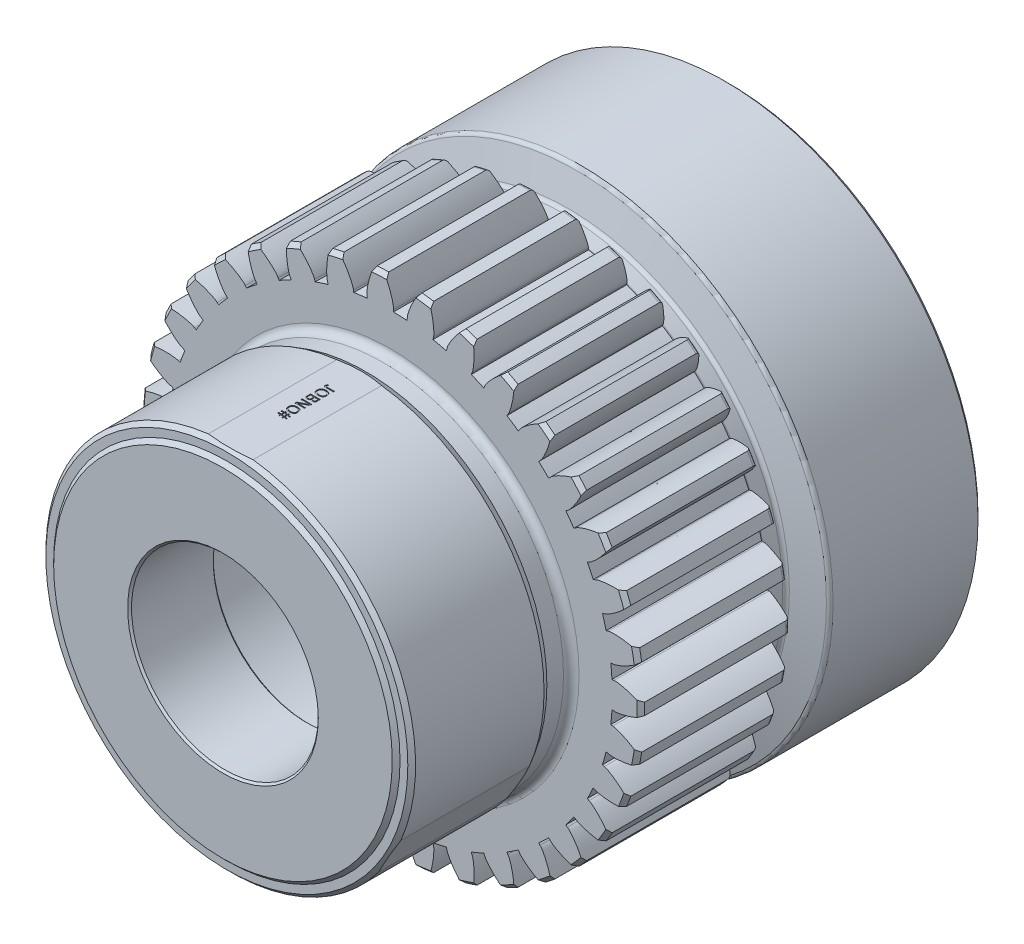
SolidWorks part; units mm, degrees
ref_plane "Front Plane" through (0, 0, 0) normal (0, 0, 1) x (1, 0, 0)
ref_plane "Top Plane" through (0, 0, 0) normal (0, 1, 0) x (1, 0, 0)
ref_plane "Right Plane" through (0, 0, 0) normal (1, 0, 0) x (0, 0, -1)
sketch "Sketch1" plane through (0, 0, 0) normal (1, 0, 0) x (0, 0, -1)
  line L0 (0, 0) -> (130, 0) construction
  line L1 (0.5, 24) -> (0, 24.5)
  line L2 (0, 24.5) -> (0, 43.5)
  line L3 (0, 43.5) -> (1, 44.5)
  line L4 (1, 44.5) -> (1, 46.5)
  line L5 (1, 46.5) -> (2, 47.5)
  line L6 (2, 47.5) -> (35, 47.5)
  line L7 (35, 47.5) -> (36.7321, 46.5)
  line L8 (36.7321, 46.5) -> (41, 46.5)
  line L9 (43, 48.5) -> (43, 63.375)
  line L10 (44, 64.375) -> (80.2327, 64.375)
  line L11 (81.1986, 63.6338) -> (83.0455, 56.7412)
  line L12 (84.0114, 56) -> (87.8211, 56)
  line L13 (88.7871, 56.7412) -> (90.8014, 64.2588)
  line L14 (91.7673, 65) -> (129, 65)
  line L15 (129, 65) -> (130, 64)
  line L16 (130, 64) -> (130, 48.3)
  line L17 (130, 48.3) -> (129.5, 47.8)
  line L18 (129.5, 47.8) -> (115, 47.8)
  line L19 (115, 47.8) -> (114.0082, 45.075)
  line L20 (114.0082, 45.075) -> (83.5, 45.075)
  line L21 (83.5, 45.075) -> (75.6324, 47.6974)
  line L22 (73, 45.8) -> (73, 45.5)
  line L23 (72, 44.5) -> (61.8229, 44.5)
  line L24 (58.5, 33.0774) -> (57.5, 32.5)
  line L25 (58.5, 43) -> (58.5, 33.0774)
  line L26 (57.5, 32.5) -> (25.3229, 32.5)
  line L27 (22, 31) -> (22, 24.5)
  line L28 (22, 24.5) -> (21.5, 24)
  line L29 (21.5, 24) -> (0.5, 24)
  line L30 (43, 63.375) -> (44, 64.375)
  line L31 (73, 45.5) -> (72, 44.5)
  arc A0 (61.8229, 44.5) -> (58.5, 43) centre (60.5, 43) ccw
  arc A1 (75.6324, 47.6974) -> (73, 45.8) centre (75, 45.8) ccw
  arc A2 (25.3229, 32.5) -> (22, 31) centre (24, 31) ccw
  arc A3 (90.8014, 64.2588) -> (91.7673, 65) centre (91.7673, 64) cw
  arc A4 (87.8211, 56) -> (88.7871, 56.7412) centre (87.8211, 57) ccw
  arc A5 (83.0455, 56.7412) -> (84.0114, 56) centre (84.0114, 57) ccw
  arc A6 (80.2327, 64.375) -> (81.1986, 63.6338) centre (80.2327, 63.375) cw
  arc A7 (41, 46.5) -> (43, 48.5) centre (41, 48.5) ccw
  point P26 (73, 44.5)
  point P29 (58.5, 32.5)
  point P44 (91, 65)
  point P51 (81, 64.375)
  point P54 (0, 24)
  dimension "D28" = 2
  dimension "D39" = 2
  dimension "D50" = 2
  dimension "D51" = 33
  dimension "D53" = 1
  dimension "D6" = 2
  dimension "D54" = 1
  dimension "D1" = 130
  dimension "D2" = 45
  dimension "D3" = 1
  dimension "D5" = 45
  dimension "D7" = 0.5
  dimension "D8" = 24
  dimension "D9" = 43.5
  dimension "D10" = 47.5
  dimension "D11" = 45
  dimension "D12" = 1
  dimension "D13" = 30
  dimension "D14" = 43
  dimension "D15" = 35
  dimension "D16" = 46.5
  dimension "D17" = 45
  dimension "D18" = 1
  dimension "D19" = 64.375
  dimension "D20" = 15
  dimension "D21" = 15
  dimension "D22" = 10
  dimension "D23" = 38
  dimension "D24" = 39
  dimension "D25" = 1
  dimension "D26" = 65
  dimension "D27" = 56
  dimension "D29" = 45
  dimension "D30" = 0.5
  dimension "D31" = 45
  dimension "D32" = 20
  dimension "D33" = 47.8
  dimension "D34" = 47.8
  dimension "D35" = 45.075
  dimension "D36" = 15
  dimension "D37" = 46.5
  dimension "D38" = 44.5
  dimension "D40" = 57
  dimension "D41" = 18.434
  dimension "D42" = 1
  dimension "D43" = 45
  dimension "D44" = 71.5
  dimension "D45" = 1
  dimension "D46" = 30
  dimension "D47" = 32.5
  dimension "D48" = 3.3229
  dimension "D49" = 108
  dimension "D52" = 3.3229
revolve "Revolve1" add sketch "Sketch1" angle 360 about L0
sketch "Sketch2" plane through (0, 0, 0) normal (0, 0, 1) x (1, 0, 0)
  line L1 (-24.3996, 56.4945) -> (24.3996, 56.4945)
  line L2 (-24.3996, 56.4945) -> (-24.3996, 47.15)
  line L3 (-24.3996, 47.15) -> (24.3996, 47.15)
  line L4 (24.3996, 56.4945) -> (24.3996, 47.15)
  line L5 (-24.3996, 56.4945) -> (24.3996, 47.15) construction
  line L6 (-24.3996, 47.15) -> (24.3996, 56.4945) construction
  point P0 (0, 51.8223)
  dimension "D1" = 47.15
extrude "Cut-Extrude1" cut sketch "Sketch2" against normal blind 40
pattern_circular "CirPattern1" count 3 over 360 about axis through (0, 0, 0) along (0, 0, 1) of "Cut-Extrude1"
sketch "Sketch4" plane through (0, 0, 0) normal (0, 0, 1) x (1, 0, 0)
  line L0 (0, 0) -> (0, 61.25) construction
  line L1 (-41.3582, 61.25) -> (56.4132, 61.25) construction
  line L2 (0, 61.25) -> (53.2337, 80.6255) construction
  line L3 (0, 61.25) -> (-99.5288, 25.0245) construction
  line L4 (0, 0) -> (-19.6854, 54.0851) construction
  line L5 (0, 0) -> (-15.709, 55.3709) construction
  line L6 (0, 0) -> (-11.6498, 56.3648) construction
  line L7 (0, 0) -> (-7.5293, 57.0616) construction
  line L8 (0, 0) -> (-3.369, 57.4575) construction
  line L9 (0, 0) -> (0.8091, 57.5505) construction
  line L10 (-15.709, 55.3709) -> (0.4231, 59.9477) construction
  line L11 (-11.6498, 56.3648) -> (0.6783, 58.9129) construction
  line L12 (-7.5293, 57.0616) -> (0.8072, 58.1616) construction
  line L13 (0, 0) -> (-23.5579, 52.5142) construction
  line L14 (0, 0) -> (-27.3063, 50.6663) construction
  line L15 (-30.9107, 48.5514) -> (0, 0) construction
  line L16 (0, 0) -> (-34.3522, 46.1805) construction
  line L17 (-37.6125, 43.5662) -> (0, 0) construction
  line L18 (-23.5579, 52.5142) -> (-0.6305, 62.7994) construction
  line L19 (-27.3063, 50.6663) -> (-1.506, 64.5713) construction
  line L20 (-30.9107, 48.5514) -> (-2.6614, 66.5366) construction
  line L21 (-34.3522, 46.1805) -> (-4.1285, 68.663) construction
  line L22 (-37.6125, 43.5662) -> (-5.899, 70.9458) construction
  circle A0 centre (0, 0) radius 61.25 construction
  circle A1 centre (0, 0) radius 57.5562 construction
  point P15 (-15.7575, 55.5148)
  point P16 (-11.8295, 56.9444)
  point P17 (-7.9016, 58.374)
  point P18 (-3.9737, 59.8037)
  point P27 (-39.3707, 46.9202)
  point P28 (-23.6133, 52.6555)
  point P29 (-27.5412, 51.2258)
  point P30 (-31.4691, 49.7962)
  point P31 (-35.397, 48.3665)
  dimension "D1" = 122.5
  dimension "D2" = 20
  dimension "D3" = 20.9487
  dimension "D4" = 4.18
  dimension "D5" = 4.18
  dimension "D6" = 4.18
  dimension "D7" = 4.18
  dimension "D8" = 4.2287
  dimension "D9" = 16.7687
  dimension "D10" = 12.5887
  dimension "D11" = 8.4087
  dimension "D17" = 16.7687
  dimension "D18" = 12.5887
  dimension "D19" = 8.4087
  dimension "D20" = 4.18
  dimension "D21" = 4.18
  dimension "D22" = 4.18
  dimension "D23" = 4.18
  dimension "D24" = 4.2287
  dimension "D25" = 25.1287
  dimension "D26" = 29.3087
  dimension "D27" = 33.4887
  dimension "D28" = 37.6687
  dimension "D29" = 41.8975
  dimension "D35" = 25.1287
  dimension "D36" = 29.3087
  dimension "D37" = 33.4887
  dimension "D38" = 37.6687
  dimension "D39" = 41.8975
  dimension "D12" = 4.18
  dimension "D13" = 4.18
  dimension "D14" = 4.18
  dimension "D15" = 4.18
  dimension "D16" = 4.18
  dimension "D30" = 4.18
  dimension "D31" = 4.18
  dimension "D32" = 4.18
  dimension "D33" = 4.18
  dimension "D34" = 4.18
sketch "Sketch5" plane through (0, 0, 0) normal (0, 0, 1) x (1, 0, 0)
  line L0 (0.8091, 57.5505) -> (0.802, 57.0444)
  line L1 (0, 0) -> (-2.7466, 61.1884) construction
  line L2 (-5.962, 57.2466) -> (-5.9096, 56.7431)
  line L3 (4.3556, 57.3911) -> (4.3173, 56.8864)
  line L4 (11.0721, 56.4812) -> (10.9747, 55.9844)
  line L5 (14.5332, 55.6911) -> (14.4054, 55.2013)
  line L6 (20.9793, 53.5965) -> (20.7948, 53.1251)
  line L7 (24.2436, 52.2011) -> (24.0304, 51.7421)
  line L8 (30.2122, 48.9892) -> (29.9465, 48.5583)
  line L9 (33.1749, 47.0334) -> (32.8832, 46.6197)
  line L10 (38.474, 42.8073) -> (38.1356, 42.4308)
  line L11 (41.0399, 40.3539) -> (40.679, 39.999)
  line L12 (45.4992, 35.2496) -> (45.0991, 34.9396)
  line L13 (47.5859, 32.3775) -> (47.1674, 32.0927)
  line L14 (51.0621, 26.5589) -> (50.613, 26.3253)
  line L15 (52.6023, 23.3604) -> (52.1397, 23.1549)
  line L16 (54.9838, 17.0146) -> (54.5002, 16.865)
  line L17 (55.9282, 13.5924) -> (55.4363, 13.4729)
  line L18 (57.1382, 6.9234) -> (56.6357, 6.8625)
  line L19 (57.4564, 3.3876) -> (56.9511, 3.3579)
  line L20 (57.4562, -3.3903) -> (56.9509, -3.3604)
  line L21 (57.1379, -6.926) -> (56.6354, -6.8651)
  line L22 (55.9275, -13.595) -> (55.4357, -13.4754)
  line L23 (54.983, -17.0171) -> (54.4995, -16.8674)
  line L24 (52.6013, -23.3628) -> (52.1387, -23.1573)
  line L25 (51.0609, -26.5612) -> (50.6118, -26.3276)
  line L26 (47.5844, -32.3796) -> (47.1659, -32.0949)
  line L27 (45.4976, -35.2516) -> (45.0975, -34.9416)
  line L28 (41.0381, -40.3558) -> (40.6772, -40.0009)
  line L29 (38.472, -42.8091) -> (38.1337, -42.4326)
  line L30 (33.1728, -47.0349) -> (32.881, -46.6212)
  line L31 (30.2099, -48.9905) -> (29.9442, -48.5597)
  line L32 (24.2413, -52.2022) -> (24.0281, -51.7432)
  line L33 (20.9768, -53.5974) -> (20.7924, -53.1261)
  line L34 (14.5306, -55.6918) -> (14.4028, -55.202)
  line L35 (11.0695, -56.4817) -> (10.9722, -55.9849)
  line L36 (4.353, -57.3913) -> (4.3147, -56.8866)
  line L37 (0.8065, -57.5505) -> (0.7994, -57.0444)
  line L38 (-5.9646, -57.2463) -> (-5.9122, -56.7428)
  line L39 (-9.4825, -56.7697) -> (-9.3991, -56.2704)
  line L40 (-16.0905, -55.2613) -> (-15.949, -54.7753)
  line L41 (-19.4668, -54.1642) -> (-19.2956, -53.6878)
  line L42 (-25.6992, -51.5002) -> (-25.4732, -51.0472)
  line L43 (-28.8253, -49.8178) -> (-28.5718, -49.3797)
  line L44 (-34.4819, -46.0838) -> (-34.1786, -45.6785)
  line L45 (-37.2574, -43.8703) -> (-36.9297, -43.4844)
  line L46 (-42.1563, -39.1862) -> (-41.7856, -38.8416)
  line L47 (-44.492, -36.5127) -> (-44.1007, -36.1916)
  line L48 (-48.4758, -31.0292) -> (-48.0495, -30.7563)
  line L49 (-50.2966, -27.9816) -> (-49.8542, -27.7355)
  line L50 (-53.2373, -21.8748) -> (-52.7691, -21.6824)
  line L51 (-54.4846, -18.5511) -> (-54.0054, -18.3879)
  line L52 (-56.2876, -12.0174) -> (-55.7926, -11.9117)
  line L53 (-56.9214, -8.5244) -> (-56.4208, -8.4494)
  line L54 (-57.5288, -1.7737) -> (-57.0229, -1.7581)
  line L55 (-57.5288, 1.7763) -> (-57.0228, 1.7607)
  line L56 (-56.921, 8.5269) -> (-56.4204, 8.452)
  line L57 (-56.2871, 12.02) -> (-55.7921, 11.9142)
  line L58 (-54.4837, 18.5536) -> (-54.0046, 18.3904)
  line L59 (-53.2363, 21.8772) -> (-52.7681, 21.6848)
  line L60 (-50.2953, 27.9838) -> (-49.853, 27.7377)
  line L61 (-48.4744, 31.0314) -> (-48.0481, 30.7585)
  line L62 (-44.4903, 36.5147) -> (-44.0991, 36.1936)
  line L63 (-42.1545, 39.1881) -> (-41.7838, 38.8435)
  line L64 (-37.2554, 43.872) -> (-36.9278, 43.4861)
  line L65 (-34.4798, 46.0853) -> (-34.1766, 45.68)
  line L66 (-28.823, 49.8191) -> (-28.5696, 49.381)
  line L67 (-25.6968, 51.5013) -> (-25.4708, 51.0484)
  line L68 (-19.4643, 54.1651) -> (-19.2931, 53.6887)
  line L69 (-16.088, 55.262) -> (-15.9465, 54.776)
  line L70 (-9.48, 56.7701) -> (-9.3966, 56.2708)
  arc A0 (-15.6828, 62.8221) -> (-24.2355, 60.0433) centre (0, 0) ccw
  arc A1 (-15.9465, 54.776) -> (-19.2931, 53.6887) centre (0, 0) ccw
  circle A2 centre (0, 0) radius 61.25 construction
  arc A3 (-25.4708, 51.0484) -> (-28.5696, 49.381) centre (0, 0) ccw
  arc A4 (-26.6481, 59.0122) -> (-34.5672, 54.751) centre (0, 0) ccw
  arc A5 (-36.7569, 53.3057) -> (-43.7878, 47.6989) centre (0, 0) ccw
  arc A6 (-34.1766, 45.68) -> (-36.9278, 43.4861) centre (0, 0) ccw
  arc A7 (-41.7838, 38.8435) -> (-44.0991, 36.1936) centre (0, 0) ccw
  arc A8 (-45.6843, 45.8858) -> (-51.6011, 39.1138) centre (0, 0) ccw
  arc A9 (-53.1434, 36.9912) -> (-57.7559, 29.2715) centre (0, 0) ccw
  arc A10 (-48.0481, 30.7585) -> (-49.853, 27.7377) centre (0, 0) ccw
  arc A11 (-52.7681, 21.6848) -> (-54.0046, 18.3904) centre (0, 0) ccw
  arc A12 (-58.8943, 26.9076) -> (-62.0544, 18.4884) centre (0, 0) ccw
  arc A13 (-55.7921, 11.9142) -> (-56.4204, 8.452) centre (0, 0) ccw
  arc A14 (-62.7524, 15.9592) -> (-64.3583, 7.111) centre (0, 0) ccw
  arc A15 (-64.5936, 4.4978) -> (-64.5938, -4.4949) centre (0, 0) ccw
  arc A16 (-57.0228, 1.7607) -> (-57.0229, -1.7581) centre (0, 0) ccw
  arc A17 (-56.4208, -8.4494) -> (-55.7926, -11.9117) centre (0, 0) ccw
  arc A18 (-64.3587, -7.1081) -> (-62.7532, -15.9563) centre (0, 0) ccw
  arc A19 (-54.0054, -18.3879) -> (-52.7691, -21.6824) centre (0, 0) ccw
  arc A20 (-62.0552, -18.4855) -> (-58.8956, -26.9049) centre (0, 0) ccw
  arc A21 (-57.7572, -29.2688) -> (-53.145, -36.9888) centre (0, 0) ccw
  arc A22 (-49.8542, -27.7355) -> (-48.0495, -30.7563) centre (0, 0) ccw
  arc A23 (-44.1007, -36.1916) -> (-41.7856, -38.8416) centre (0, 0) ccw
  arc A24 (-51.6029, -39.1114) -> (-45.6864, -45.8837) centre (0, 0) ccw
  arc A25 (-43.79, -47.6969) -> (-36.7593, -53.304) centre (0, 0) ccw
  arc A26 (-36.9297, -43.4844) -> (-34.1786, -45.6785) centre (0, 0) ccw
  arc A27 (-28.5718, -49.3797) -> (-25.4732, -51.0472) centre (0, 0) ccw
  arc A28 (-34.5697, -54.7494) -> (-26.6508, -59.011) centre (0, 0) ccw
  arc A29 (-24.2382, -60.0422) -> (-15.6857, -62.8214) centre (0, 0) ccw
  arc A30 (-19.2956, -53.6878) -> (-15.949, -54.7753) centre (0, 0) ccw
  arc A31 (-9.3991, -56.2704) -> (-5.9122, -56.7428) centre (0, 0) ccw
  arc A32 (-13.1277, -63.4052) -> (-4.2164, -64.6126) centre (0, 0) ccw
  arc A33 (0.7994, -57.0444) -> (4.3147, -56.8866) centre (0, 0) ccw
  arc A34 (-1.5953, -64.7303) -> (7.3884, -64.3271) centre (0, 0) ccw
  arc A35 (9.9884, -63.975) -> (18.7557, -61.9741) centre (0, 0) ccw
  arc A36 (10.9722, -55.9849) -> (14.4028, -55.202) centre (0, 0) ccw
  arc A37 (20.7924, -53.1261) -> (24.0281, -51.7432) centre (0, 0) ccw
  arc A38 (21.251, -61.1634) -> (29.5202, -57.6292) centre (0, 0) ccw
  arc A39 (31.8306, -56.3859) -> (39.3358, -51.432) centre (0, 0) ccw
  arc A40 (29.9442, -48.5597) -> (32.881, -46.6212) centre (0, 0) ccw
  arc A41 (38.1337, -42.4326) -> (40.6772, -40.0009) centre (0, 0) ccw
  arc A42 (41.3872, -49.7962) -> (47.8872, -43.5818) centre (0, 0) ccw
  arc A43 (49.6135, -41.606) -> (54.8995, -34.3308) centre (0, 0) ccw
  arc A44 (45.0975, -34.9416) -> (47.1659, -32.0949) centre (0, 0) ccw
  arc A45 (50.6118, -26.3276) -> (52.1387, -23.1573) centre (0, 0) ccw
  arc A46 (56.2453, -32.0785) -> (60.1473, -23.9764) centre (0, 0) ccw
  arc A47 (61.0692, -21.52) -> (63.4618, -12.8514) centre (0, 0) ccw
  arc A48 (54.4995, -16.8674) -> (55.4357, -13.4754) centre (0, 0) ccw
  arc A49 (56.6354, -6.8651) -> (56.9509, -3.3604) centre (0, 0) ccw
  arc A50 (63.9304, -10.2699) -> (64.7367, -1.3133) centre (0, 0) ccw
  arc A51 (64.7367, 1.3104) -> (63.9308, 10.2669) centre (0, 0) ccw
  arc A52 (56.9511, 3.3579) -> (56.6357, 6.8625) centre (0, 0) ccw
  arc A53 (55.4363, 13.4729) -> (54.5002, 16.865) centre (0, 0) ccw
  arc A54 (63.4624, 12.8485) -> (61.0702, 21.5172) centre (0, 0) ccw
  arc A55 (60.1484, 23.9737) -> (56.2467, 32.076) centre (0, 0) ccw
  arc A56 (52.1397, 23.1549) -> (50.613, 26.3253) centre (0, 0) ccw
  arc A57 (47.1674, 32.0927) -> (45.0991, 34.9396) centre (0, 0) ccw
  arc A58 (54.9011, 34.3283) -> (49.6154, 41.6037) centre (0, 0) ccw
  arc A59 (47.8892, 43.5796) -> (41.3895, 49.7943) centre (0, 0) ccw
  arc A60 (40.679, 39.999) -> (38.1356, 42.4308) centre (0, 0) ccw
  arc A61 (32.8832, 46.6197) -> (29.9465, 48.5583) centre (0, 0) ccw
  arc A62 (39.3382, 51.4302) -> (31.8332, 56.3845) centre (0, 0) ccw
  arc A63 (29.5228, 57.6278) -> (21.2538, 61.1624) centre (0, 0) ccw
  arc A64 (24.0304, 51.7421) -> (20.7948, 53.1251) centre (0, 0) ccw
  arc A65 (14.4054, 55.2013) -> (10.9747, 55.9844) centre (0, 0) ccw
  arc A66 (18.7585, 61.9732) -> (9.9913, 63.9745) centre (0, 0) ccw
  arc A67 (7.3913, 64.3268) -> (-1.5924, 64.7304) centre (0, 0) ccw
  arc A68 (4.3173, 56.8864) -> (0.802, 57.0444) centre (0, 0) ccw
  arc A69 (-5.9096, 56.7431) -> (-9.3966, 56.2708) centre (0, 0) ccw
  arc A70 (-4.2135, 64.6128) -> (-13.1249, 63.4058) centre (0, 0) ccw
  spline S0 degree 3 poles (0.8091, 57.5505) (0.8594, 58.0118) (0.7107, 58.8161) (0.4113, 60.0491) (-0.0185, 61.3513) (-0.6518, 62.9008) (-1.2204, 64.0452) (-1.5634, 64.6774) (-1.5924, 64.7304) knots 0 0 0 0 0.090296 0.16037 0.250399 0.360381 0.490319 0.502221 0.502221 0.502221 0.502221
  spline S1 degree 3 poles (-5.962, 57.2466) (-6.0534, 57.7015) (-5.9774, 58.5159) (-5.7897, 59.7707) (-5.4783, 61.1062) (-4.9864, 62.7062) (-4.5226, 63.897) (-4.2376, 64.5574) (-4.2135, 64.6128) knots 0 0 0 0 0.090296 0.16037 0.250399 0.360381 0.490319 0.502221 0.502221 0.502221 0.502221
  spline S2 degree 3 poles (4.3556, 57.3911) (4.3469, 57.8551) (4.567, 58.6429) (4.9758, 59.844) (5.5207, 61.1024) (6.2904, 62.5889) (6.9593, 63.6777) (7.3577, 64.2766) (7.3913, 64.3268) knots 0 0 0 0 0.090296 0.16037 0.250399 0.360381 0.490319 0.502221 0.502221 0.502221 0.502221
  spline S3 degree 3 poles (11.0721, 56.4812) (11.2039, 56.926) (11.2013, 57.744) (11.1269, 59.0106) (10.9365, 60.3686) (10.5901, 62.0063) (10.235, 63.2339) (10.0103, 63.9172) (9.9913, 63.9745) knots 0 0 0 0 0.090296 0.16037 0.250399 0.360381 0.490319 0.502221 0.502221 0.502221 0.502221
  spline S4 degree 3 poles (14.5332, 55.6911) (14.6074, 56.1491) (14.9647, 56.885) (15.5814, 57.9938) (16.3422, 59.1347) (17.365, 60.4598) (18.2176, 61.4117) (18.7165, 61.9299) (18.7585, 61.9732) knots 0 0 0 0 0.090296 0.16037 0.250399 0.360381 0.490319 0.502221 0.502221 0.502221 0.502221
  spline S5 degree 3 poles (20.9793, 53.5965) (21.1884, 54.0107) (21.3319, 54.816) (21.4848, 56.0755) (21.54, 57.4457) (21.4916, 59.1189) (21.3613, 60.3901) (21.2623, 61.1026) (21.2538, 61.1624) knots 0 0 0 0 0.090296 0.16037 0.250399 0.360381 0.490319 0.502221 0.502221 0.502221 0.502221
  spline S6 degree 3 poles (24.2436, 52.2011) (24.3985, 52.6385) (24.8814, 53.2987) (25.6862, 54.2797) (26.6385, 55.2664) (27.8814, 56.3876) (28.8903, 57.1719) (29.4737, 57.5927) (29.5228, 57.6278) knots 0 0 0 0 0.090296 0.16037 0.250399 0.360381 0.490319 0.502221 0.502221 0.502221 0.502221
  spline S7 degree 3 poles (30.2122, 48.9892) (30.4919, 49.3594) (30.7769, 50.1261) (31.1522, 51.3381) (31.4512, 52.6764) (31.7023, 54.3314) (31.8011, 55.6054) (31.8309, 56.3242) (31.8332, 56.3845) knots 0 0 0 0 0.090296 0.16037 0.250399 0.360381 0.490319 0.502221 0.502221 0.502221 0.502221
  spline S8 degree 3 poles (33.1749, 47.0334) (33.4054, 47.4361) (33.9984, 47.9995) (34.9654, 48.8209) (36.0786, 49.6217) (37.5017, 50.503) (38.6344, 51.0946) (39.2836, 51.4044) (39.3382, 51.4302) knots 0 0 0 0 0.090296 0.16037 0.250399 0.360381 0.490319 0.502221 0.502221 0.502221 0.502221
  spline S9 degree 3 poles (38.474, 42.8073) (38.8153, 43.1216) (39.2326, 43.8251) (39.8184, 44.9506) (40.3515, 46.214) (40.894, 47.7976) (41.2188, 49.0335) (41.3764, 49.7354) (41.3895, 49.7943) knots 0 0 0 0 0.090296 0.16037 0.250399 0.360381 0.490319 0.502221 0.502221 0.502221 0.502221
  spline S10 degree 3 poles (41.0399, 40.3539) (41.3386, 40.709) (42.0227, 41.1574) (43.1208, 41.793) (44.3591, 42.3822) (45.9167, 42.9952) (47.1369, 43.375) (47.8309, 43.5639) (47.8892, 43.5796) knots 0 0 0 0 0.090296 0.16037 0.250399 0.360381 0.490319 0.502221 0.502221 0.502221 0.502221
  spline S11 degree 3 poles (45.4992, 35.2496) (45.8912, 35.4979) (46.4274, 36.1156) (47.2047, 37.1184) (47.9549, 38.2663) (48.7715, 39.7276) (49.3117, 40.8856) (49.5921, 41.5481) (49.6154, 41.6037) knots 0 0 0 0 0.090296 0.16037 0.250399 0.360381 0.490319 0.502221 0.502221 0.502221 0.502221
  spline S12 degree 3 poles (47.5859, 32.3775) (47.9431, 32.6735) (48.6963, 32.9926) (49.8903, 33.4219) (51.2138, 33.7805) (52.8559, 34.1055) (54.1243, 34.2614) (54.8409, 34.3233) (54.9011, 34.3283) knots 0 0 0 0 0.090296 0.16037 0.250399 0.360381 0.490319 0.502221 0.502221 0.502221 0.502221
  spline S13 degree 3 poles (51.0621, 26.5589) (51.4921, 26.7332) (52.13, 27.2452) (53.0739, 28.0932) (54.0169, 29.0887) (55.0813, 30.3807) (55.8196, 31.4237) (56.2138, 32.0254) (56.2467, 32.076) knots 0 0 0 0 0.090296 0.16037 0.250399 0.360381 0.490319 0.502221 0.502221 0.502221 0.502221
  spline S14 degree 3 poles (52.6023, 23.3604) (53.0068, 23.5879) (53.8048, 23.7673) (55.0562, 23.9765) (56.4226, 24.0931) (58.0963, 24.1196) (59.3721, 24.0465) (60.0883, 23.9795) (60.1484, 23.9737) knots 0 0 0 0 0.090296 0.16037 0.250399 0.360381 0.490319 0.502221 0.502221 0.502221 0.502221
  spline S15 degree 3 poles (54.9838, 17.0146) (55.438, 17.1093) (56.1571, 17.4992) (57.2372, 18.165) (58.3428, 18.9761) (59.6208, 20.0573) (60.5335, 20.9517) (61.0288, 21.4733) (61.0702, 21.5172) knots 0 0 0 0 0.090296 0.16037 0.250399 0.360381 0.490319 0.502221 0.502221 0.502221 0.502221
  spline S16 degree 3 poles (55.9282, 13.5924) (56.3667, 13.7441) (57.184, 13.7781) (58.4526, 13.7605) (59.8178, 13.6312) (61.4694, 13.3585) (62.7116, 13.0588) (63.4043, 12.865) (63.4624, 12.8485) knots 0 0 0 0 0.090296 0.16037 0.250399 0.360381 0.490319 0.502221 0.502221 0.502221 0.502221
  spline S17 degree 3 poles (57.1382, 6.9234) (57.6021, 6.9355) (58.3792, 7.1908) (59.5608, 7.653) (60.7936, 8.2537) (62.244, 9.0892) (63.3018, 9.8063) (63.8822, 10.2312) (63.9308, 10.2669) knots 0 0 0 0 0.090296 0.16037 0.250399 0.360381 0.490319 0.502221 0.502221 0.502221 0.502221
  spline S18 degree 3 poles (57.4564, 3.3876) (57.915, 3.4585) (58.7252, 3.3461) (59.9703, 3.1023) (61.2905, 2.7313) (62.8668, 2.1681) (64.0355, 1.6513) (64.6825, 1.3369) (64.7367, 1.3104) knots 0 0 0 0 0.090296 0.16037 0.250399 0.360381 0.490319 0.502221 0.502221 0.502221 0.502221
  spline S19 degree 3 poles (57.4562, -3.3903) (57.9148, -3.4612) (58.725, -3.3488) (59.9702, -3.105) (61.2903, -2.7341) (62.8667, -2.1709) (64.0355, -1.6542) (64.6825, -1.3399) (64.7367, -1.3133) knots 0 0 0 0 0.090296 0.16037 0.250399 0.360381 0.490319 0.502221 0.502221 0.502221 0.502221
  spline S20 degree 3 poles (57.1379, -6.926) (57.6018, -6.9382) (58.3789, -7.1934) (59.5605, -7.6557) (60.7932, -8.2564) (62.2436, -9.0921) (63.3013, -9.8092) (63.8818, -10.2341) (63.9304, -10.2699) knots 0 0 0 0 0.090296 0.16037 0.250399 0.360381 0.490319 0.502221 0.502221 0.502221 0.502221
  spline S21 degree 3 poles (55.9275, -13.595) (56.3661, -13.7466) (57.1833, -13.7807) (58.452, -13.7632) (59.8172, -13.6339) (61.4688, -13.3613) (62.711, -13.0616) (63.4037, -12.8678) (63.4618, -12.8514) knots 0 0 0 0 0.090296 0.16037 0.250399 0.360381 0.490319 0.502221 0.502221 0.502221 0.502221
  spline S22 degree 3 poles (54.983, -17.0171) (55.4372, -17.1119) (56.1563, -17.5018) (57.2364, -18.1676) (58.342, -18.9788) (59.6199, -20.06) (60.5325, -20.9544) (61.0278, -21.4761) (61.0692, -21.52) knots 0 0 0 0 0.090296 0.16037 0.250399 0.360381 0.490319 0.502221 0.502221 0.502221 0.502221
  spline S23 degree 3 poles (52.6013, -23.3628) (53.0057, -23.5903) (53.8037, -23.7698) (55.0551, -23.979) (56.4215, -24.0956) (58.0952, -24.1223) (59.371, -24.0492) (60.0872, -23.9822) (60.1473, -23.9764) knots 0 0 0 0 0.090296 0.16037 0.250399 0.360381 0.490319 0.502221 0.502221 0.502221 0.502221
  spline S24 degree 3 poles (51.0609, -26.5612) (51.4909, -26.7356) (52.1288, -27.2476) (53.0726, -28.0956) (54.0156, -29.0912) (55.0799, -30.3832) (55.8182, -31.4262) (56.2124, -32.0279) (56.2453, -32.0785) knots 0 0 0 0 0.090296 0.16037 0.250399 0.360381 0.490319 0.502221 0.502221 0.502221 0.502221
  spline S25 degree 3 poles (47.5844, -32.3796) (47.9417, -32.6757) (48.6948, -32.9948) (49.8888, -33.4241) (51.2123, -33.7828) (52.8544, -34.1079) (54.1227, -34.2638) (54.8394, -34.3258) (54.8995, -34.3308) knots 0 0 0 0 0.090296 0.16037 0.250399 0.360381 0.490319 0.502221 0.502221 0.502221 0.502221
  spline S26 degree 3 poles (45.4976, -35.2516) (45.8896, -35.5) (46.4258, -36.1177) (47.203, -37.1205) (47.9531, -38.2685) (48.7696, -39.7298) (49.3098, -40.8879) (49.5902, -41.5503) (49.6135, -41.606) knots 0 0 0 0 0.090296 0.16037 0.250399 0.360381 0.490319 0.502221 0.502221 0.502221 0.502221
  spline S27 degree 3 poles (41.0381, -40.3558) (41.3367, -40.7109) (42.0208, -41.1593) (43.1189, -41.795) (44.3572, -42.3842) (45.9148, -42.9973) (47.1349, -43.3772) (47.829, -43.5661) (47.8872, -43.5818) knots 0 0 0 0 0.090296 0.16037 0.250399 0.360381 0.490319 0.502221 0.502221 0.502221 0.502221
  spline S28 degree 3 poles (38.472, -42.8091) (38.8134, -43.1234) (39.2306, -43.8269) (39.8163, -44.9524) (40.3494, -46.2159) (40.8919, -47.7995) (41.2166, -49.0354) (41.3742, -49.7373) (41.3872, -49.7962) knots 0 0 0 0 0.090296 0.16037 0.250399 0.360381 0.490319 0.502221 0.502221 0.502221 0.502221
  spline S29 degree 3 poles (33.1728, -47.0349) (33.4032, -47.4376) (33.9963, -48.001) (34.9632, -48.8225) (36.0763, -49.6234) (37.4994, -50.5047) (38.6321, -51.0963) (39.2813, -51.4062) (39.3358, -51.432) knots 0 0 0 0 0.090296 0.16037 0.250399 0.360381 0.490319 0.502221 0.502221 0.502221 0.502221
  spline S30 degree 3 poles (30.2099, -48.9905) (30.4897, -49.3608) (30.7746, -50.1275) (31.1499, -51.3395) (31.4488, -52.6778) (31.6998, -54.3328) (31.7986, -55.6069) (31.8283, -56.3256) (31.8306, -56.3859) knots 0 0 0 0 0.090296 0.16037 0.250399 0.360381 0.490319 0.502221 0.502221 0.502221 0.502221
  spline S31 degree 3 poles (24.2413, -52.2022) (24.3961, -52.6397) (24.879, -53.2999) (25.6837, -54.2808) (26.636, -55.2676) (27.8788, -56.3889) (28.8877, -57.1732) (29.4711, -57.594) (29.5202, -57.6292) knots 0 0 0 0 0.090296 0.16037 0.250399 0.360381 0.490319 0.502221 0.502221 0.502221 0.502221
  spline S32 degree 3 poles (20.9768, -53.5974) (21.186, -54.0116) (21.3294, -54.8169) (21.4823, -56.0765) (21.5374, -57.4467) (21.4889, -59.1199) (21.3586, -60.3911) (21.2595, -61.1036) (21.251, -61.1634) knots 0 0 0 0 0.090296 0.16037 0.250399 0.360381 0.490319 0.502221 0.502221 0.502221 0.502221
  spline S33 degree 3 poles (14.5306, -55.6918) (14.6049, -56.1498) (14.9621, -56.8856) (15.5788, -57.9945) (16.3395, -59.1355) (17.3622, -60.4606) (18.2148, -61.4125) (18.7137, -61.9307) (18.7557, -61.9741) knots 0 0 0 0 0.090296 0.16037 0.250399 0.360381 0.490319 0.502221 0.502221 0.502221 0.502221
  spline S34 degree 3 poles (11.0695, -56.4817) (11.2014, -56.9266) (11.1987, -57.7445) (11.1242, -59.0111) (10.9338, -60.3691) (10.5873, -62.0068) (10.2321, -63.2343) (10.0074, -63.9177) (9.9884, -63.975) knots 0 0 0 0 0.090296 0.16037 0.250399 0.360381 0.490319 0.502221 0.502221 0.502221 0.502221
  spline S35 degree 3 poles (4.353, -57.3913) (4.3442, -57.8553) (4.5644, -58.6431) (4.9731, -59.8442) (5.5179, -61.1026) (6.2875, -62.5892) (6.9564, -63.678) (7.3548, -64.2769) (7.3884, -64.3271) knots 0 0 0 0 0.090296 0.16037 0.250399 0.360381 0.490319 0.502221 0.502221 0.502221 0.502221
  spline S36 degree 3 poles (0.8065, -57.5505) (0.8567, -58.0118) (0.7081, -58.8162) (0.4086, -60.0491) (-0.0213, -61.3513) (-0.6546, -62.9008) (-1.2233, -64.0451) (-1.5664, -64.6774) (-1.5953, -64.7303) knots 0 0 0 0 0.090296 0.16037 0.250399 0.360381 0.490319 0.502221 0.502221 0.502221 0.502221
  spline S37 degree 3 poles (-5.9646, -57.2463) (-6.056, -57.7012) (-5.9801, -58.5156) (-5.7924, -59.7705) (-5.4811, -61.106) (-4.9892, -62.706) (-4.5255, -63.8968) (-4.2405, -64.5572) (-4.2164, -64.6126) knots 0 0 0 0 0.090296 0.16037 0.250399 0.360381 0.490319 0.502221 0.502221 0.502221 0.502221
  spline S38 degree 3 poles (-9.4825, -56.7697) (-9.5155, -57.2325) (-9.8053, -57.9974) (-10.3202, -59.157) (-10.9756, -60.3616) (-11.8755, -61.773) (-12.6393, -62.7975) (-13.0898, -63.3583) (-13.1277, -63.4052) knots 0 0 0 0 0.090296 0.16037 0.250399 0.360381 0.490319 0.502221 0.502221 0.502221 0.502221
  spline S39 degree 3 poles (-16.0905, -55.2613) (-16.2616, -55.6926) (-16.3324, -56.5075) (-16.3718, -57.7757) (-16.3039, -59.1453) (-16.1057, -60.8074) (-15.862, -62.0618) (-15.6995, -62.7626) (-15.6857, -62.8214) knots 0 0 0 0 0.090296 0.16037 0.250399 0.360381 0.490319 0.502221 0.502221 0.502221 0.502221
  spline S40 degree 3 poles (-19.4668, -54.1642) (-19.5818, -54.6137) (-20.0036, -55.3145) (-20.7172, -56.3636) (-21.5772, -57.4317) (-22.7146, -58.6599) (-23.6491, -59.5315) (-24.1925, -60.0028) (-24.2382, -60.0422) knots 0 0 0 0 0.090296 0.16037 0.250399 0.360381 0.490319 0.502221 0.502221 0.502221 0.502221
  spline S41 degree 3 poles (-25.6992, -51.5002) (-25.9446, -51.8939) (-26.1597, -52.6831) (-26.4249, -53.9239) (-26.6027, -55.2836) (-26.7044, -56.9544) (-26.6887, -58.2322) (-26.6539, -58.9507) (-26.6508, -59.011) knots 0 0 0 0 0.090296 0.16037 0.250399 0.360381 0.490319 0.502221 0.502221 0.502221 0.502221
  spline S42 degree 3 poles (-28.8253, -49.8178) (-29.0188, -50.2396) (-29.5589, -50.8538) (-30.4484, -51.7586) (-31.4853, -52.656) (-32.8237, -53.6613) (-33.8988, -54.3521) (-34.5176, -54.7188) (-34.5697, -54.7494) knots 0 0 0 0 0.090296 0.16037 0.250399 0.360381 0.490319 0.502221 0.502221 0.502221 0.502221
  spline S43 degree 3 poles (-34.4819, -46.0838) (-34.7937, -46.4274) (-35.1462, -47.1655) (-35.6287, -48.339) (-36.0464, -49.6451) (-36.4449, -51.2709) (-36.6575, -52.531) (-36.7516, -53.2441) (-36.7593, -53.304) knots 0 0 0 0 0.090296 0.16037 0.250399 0.360381 0.490319 0.502221 0.502221 0.502221 0.502221
  spline S44 degree 3 poles (-37.2574, -43.8703) (-37.523, -44.2507) (-38.1642, -44.7586) (-39.2009, -45.4901) (-40.3814, -46.1879) (-41.8778, -46.9381) (-43.059, -47.4257) (-43.7333, -47.6761) (-43.79, -47.6969) knots 0 0 0 0 0.090296 0.16037 0.250399 0.360381 0.490319 0.502221 0.502221 0.502221 0.502221
  spline S45 degree 3 poles (-42.1563, -39.1862) (-42.5245, -39.4686) (-43.0032, -40.1319) (-43.6874, -41.2004) (-44.3316, -42.4109) (-45.014, -43.9395) (-45.4482, -45.1413) (-45.6681, -45.8262) (-45.6864, -45.8837) knots 0 0 0 0 0.090296 0.16037 0.250399 0.360381 0.490319 0.502221 0.502221 0.502221 0.502221
  spline S46 degree 3 poles (-44.492, -36.5127) (-44.8213, -36.8396) (-45.5429, -37.2249) (-46.6935, -37.7595) (-47.9796, -38.2353) (-49.5859, -38.7062) (-50.8352, -38.9751) (-51.5434, -39.101) (-51.6029, -39.1114) knots 0 0 0 0 0.090296 0.16037 0.250399 0.360381 0.490319 0.502221 0.502221 0.502221 0.502221
  spline S47 degree 3 poles (-48.4758, -31.0292) (-48.8885, -31.2413) (-49.4779, -31.8085) (-50.342, -32.7376) (-51.192, -33.8136) (-52.1363, -35.1958) (-52.7781, -36.3008) (-53.1168, -36.9354) (-53.145, -36.9888) knots 0 0 0 0 0.090296 0.16037 0.250399 0.360381 0.490319 0.502221 0.502221 0.502221 0.502221
  spline S48 degree 3 poles (-50.2966, -27.9816) (-50.679, -28.2444) (-51.4577, -28.4946) (-52.6853, -28.8152) (-54.0357, -29.0537) (-55.7003, -29.2302) (-56.9775, -29.2718) (-57.6969, -29.2692) (-57.7572, -29.2688) knots 0 0 0 0 0.090296 0.16037 0.250399 0.360381 0.490319 0.502221 0.502221 0.502221 0.502221
  spline S49 degree 3 poles (-53.2373, -21.8748) (-53.6812, -22.0099) (-54.3624, -22.4627) (-55.3785, -23.2226) (-56.407, -24.1296) (-57.5829, -25.3209) (-58.4117, -26.2935) (-58.8582, -26.8575) (-58.8956, -26.9049) knots 0 0 0 0 0.090296 0.16037 0.250399 0.360381 0.490319 0.502221 0.502221 0.502221 0.502221
  spline S50 degree 3 poles (-54.4846, -18.5511) (-54.9078, -18.7414) (-55.7187, -18.8486) (-56.9838, -18.9448) (-58.3551, -18.9384) (-60.0245, -18.8148) (-61.2886, -18.6276) (-61.9959, -18.4967) (-62.0552, -18.4855) knots 0 0 0 0 0.090296 0.16037 0.250399 0.360381 0.490319 0.502221 0.502221 0.502221 0.502221
  spline S51 degree 3 poles (-56.2876, -12.0174) (-56.7485, -12.071) (-57.4996, -12.3949) (-58.6351, -12.9612) (-59.809, -13.6699) (-61.1787, -14.6322) (-62.1679, -15.4412) (-62.708, -15.9163) (-62.7532, -15.9563) knots 0 0 0 0 0.090296 0.16037 0.250399 0.360381 0.490319 0.502221 0.502221 0.502221 0.502221
  spline S52 degree 3 poles (-56.9214, -8.5244) (-57.3718, -8.6361) (-58.1888, -8.5967) (-59.4508, -8.4655) (-60.7989, -8.2143) (-62.4194, -7.7947) (-63.6297, -7.3848) (-64.3023, -7.1297) (-64.3587, -7.1081) knots 0 0 0 0 0.090296 0.16037 0.250399 0.360381 0.490319 0.502221 0.502221 0.502221 0.502221
  spline S53 degree 3 poles (-57.5288, -1.7737) (-57.9919, -1.7442) (-58.7888, -1.9288) (-60.0071, -2.2832) (-61.2887, -2.771) (-62.8082, -3.4731) (-63.926, -4.0925) (-64.5422, -4.4636) (-64.5938, -4.4949) knots 0 0 0 0 0.090296 0.16037 0.250399 0.360381 0.490319 0.502221 0.502221 0.502221 0.502221
  spline S54 degree 3 poles (-57.5288, 1.7763) (-57.9918, 1.7468) (-58.7887, 1.9314) (-60.007, 2.2859) (-61.2886, 2.7737) (-62.8081, 3.476) (-63.9258, 4.0954) (-64.542, 4.4665) (-64.5936, 4.4978) knots 0 0 0 0 0.090296 0.16037 0.250399 0.360381 0.490319 0.502221 0.502221 0.502221 0.502221
  spline S55 degree 3 poles (-56.921, 8.5269) (-57.3714, 8.6387) (-58.1884, 8.5994) (-59.4504, 8.4682) (-60.7985, 8.2171) (-62.419, 7.7975) (-63.6294, 7.3877) (-64.302, 7.1326) (-64.3583, 7.111) knots 0 0 0 0 0.090296 0.16037 0.250399 0.360381 0.490319 0.502221 0.502221 0.502221 0.502221
  spline S56 degree 3 poles (-56.2871, 12.02) (-56.748, 12.0736) (-57.4991, 12.3975) (-58.6345, 12.9638) (-59.8084, 13.6727) (-61.178, 14.6349) (-62.1672, 15.444) (-62.7072, 15.9192) (-62.7524, 15.9592) knots 0 0 0 0 0.090296 0.16037 0.250399 0.360381 0.490319 0.502221 0.502221 0.502221 0.502221
  spline S57 degree 3 poles (-54.4837, 18.5536) (-54.9069, 18.7439) (-55.7178, 18.8511) (-56.983, 18.9474) (-58.3542, 18.941) (-60.0236, 18.8176) (-61.2877, 18.6304) (-61.995, 18.4995) (-62.0544, 18.4884) knots 0 0 0 0 0.090296 0.16037 0.250399 0.360381 0.490319 0.502221 0.502221 0.502221 0.502221
  spline S58 degree 3 poles (-53.2363, 21.8772) (-53.6802, 22.0123) (-54.3614, 22.4651) (-55.3774, 23.2251) (-56.4059, 24.1321) (-57.5817, 25.3235) (-58.4105, 26.2962) (-58.857, 26.8602) (-58.8943, 26.9076) knots 0 0 0 0 0.090296 0.16037 0.250399 0.360381 0.490319 0.502221 0.502221 0.502221 0.502221
  spline S59 degree 3 poles (-50.2953, 27.9838) (-50.6777, 28.2467) (-51.4564, 28.497) (-52.684, 28.8176) (-54.0344, 29.0562) (-55.699, 29.2328) (-56.9762, 29.2744) (-57.6955, 29.2719) (-57.7559, 29.2715) knots 0 0 0 0 0.090296 0.16037 0.250399 0.360381 0.490319 0.502221 0.502221 0.502221 0.502221
  spline S60 degree 3 poles (-48.4744, 31.0314) (-48.8871, 31.2435) (-49.4765, 31.8107) (-50.3405, 32.7399) (-51.1904, 33.816) (-52.1347, 35.1982) (-52.7765, 36.3032) (-53.1151, 36.9378) (-53.1434, 36.9912) knots 0 0 0 0 0.090296 0.16037 0.250399 0.360381 0.490319 0.502221 0.502221 0.502221 0.502221
  spline S61 degree 3 poles (-44.4903, 36.5147) (-44.8196, 36.8416) (-45.5412, 37.2269) (-46.6918, 37.7616) (-47.9779, 38.2375) (-49.5842, 38.7084) (-50.8334, 38.9774) (-51.5417, 39.1034) (-51.6011, 39.1138) knots 0 0 0 0 0.090296 0.16037 0.250399 0.360381 0.490319 0.502221 0.502221 0.502221 0.502221
  spline S62 degree 3 poles (-42.1545, 39.1881) (-42.5227, 39.4706) (-43.0013, 40.1339) (-43.6855, 41.2024) (-44.3297, 42.4129) (-45.012, 43.9415) (-45.4461, 45.1434) (-45.666, 45.8283) (-45.6843, 45.8858) knots 0 0 0 0 0.090296 0.16037 0.250399 0.360381 0.490319 0.502221 0.502221 0.502221 0.502221
  spline S63 degree 3 poles (-37.2554, 43.872) (-37.521, 44.2524) (-38.1622, 44.7604) (-39.1989, 45.4919) (-40.3793, 46.1898) (-41.8757, 46.94) (-43.0568, 47.4277) (-43.7312, 47.6781) (-43.7878, 47.6989) knots 0 0 0 0 0.090296 0.16037 0.250399 0.360381 0.490319 0.502221 0.502221 0.502221 0.502221
  spline S64 degree 3 poles (-34.4798, 46.0853) (-34.7916, 46.429) (-35.1441, 47.1671) (-35.6265, 48.3406) (-36.0442, 49.6467) (-36.4425, 51.2726) (-36.6551, 52.5326) (-36.7492, 53.2458) (-36.7569, 53.3057) knots 0 0 0 0 0.090296 0.16037 0.250399 0.360381 0.490319 0.502221 0.502221 0.502221 0.502221
  spline S65 degree 3 poles (-28.823, 49.8191) (-29.0165, 50.2409) (-29.5566, 50.8552) (-30.446, 51.76) (-31.4829, 52.6575) (-32.8213, 53.6628) (-33.8964, 54.3536) (-34.5151, 54.7204) (-34.5672, 54.751) knots 0 0 0 0 0.090296 0.16037 0.250399 0.360381 0.490319 0.502221 0.502221 0.502221 0.502221
  spline S66 degree 3 poles (-25.6968, 51.5013) (-25.9422, 51.8951) (-26.1573, 52.6843) (-26.4225, 53.9251) (-26.6002, 55.2848) (-26.7018, 56.9557) (-26.686, 58.2334) (-26.6512, 58.9519) (-26.6481, 59.0122) knots 0 0 0 0 0.090296 0.16037 0.250399 0.360381 0.490319 0.502221 0.502221 0.502221 0.502221
  spline S67 degree 3 poles (-19.4643, 54.1651) (-19.5793, 54.6146) (-20.0011, 55.3154) (-20.7146, 56.3646) (-21.5746, 57.4327) (-22.712, 58.6609) (-23.6464, 59.5325) (-24.1898, 60.0039) (-24.2355, 60.0433) knots 0 0 0 0 0.090296 0.16037 0.250399 0.360381 0.490319 0.502221 0.502221 0.502221 0.502221
  spline S68 degree 3 poles (-16.088, 55.262) (-16.2591, 55.6933) (-16.3298, 56.5082) (-16.3691, 57.7764) (-16.3012, 59.146) (-16.1029, 60.8082) (-15.8592, 62.0626) (-15.6966, 62.7633) (-15.6828, 62.8221) knots 0 0 0 0 0.090296 0.16037 0.250399 0.360381 0.490319 0.502221 0.502221 0.502221 0.502221
  spline S69 degree 3 poles (-9.48, 56.7701) (-9.5129, 57.2329) (-9.8027, 57.9978) (-10.3175, 59.1575) (-10.9729, 60.362) (-11.8727, 61.7736) (-12.6365, 62.7981) (-13.0869, 63.3589) (-13.1249, 63.4058) knots 0 0 0 0 0.090296 0.16037 0.250399 0.360381 0.490319 0.502221 0.502221 0.502221 0.502221
  point P646 (0, 0)
  dimension "D1" = 129.5
  dimension "D2" = 114.1
  dimension "D3" = 2.7475
  dimension "D4" = 35
extrude "Cut-Extrude2" cut sketch "Sketch5" against normal blind 86
ref_plane "Rear Plane" through (0, 0, -130) normal (0, 0, -1) x (-1, 0, 0)
sketch "Sketch6" plane through (0, 0, -130) normal (0, 0, -1) x (-1, 0, 0)
  line L0 (0, 0) -> (0, 45) construction
  line L1 (-41.3582, 45) -> (56.4132, 45) construction
  line L2 (0, 45) -> (53.8737, 76.104) construction
  line L3 (0, 45) -> (-86.913, -5.1792) construction
  line L4 (0, 0) -> (-19.4856, 33.75) construction
  line L5 (0, 0) -> (-15.4674, 35.7703) construction
  line L6 (0, 0) -> (-11.2431, 37.3141) construction
  line L7 (0, 0) -> (-6.8692, 38.361) construction
  line L8 (0, 0) -> (-2.4037, 38.8969) construction
  line L9 (0, 0) -> (2.0937, 38.9149) construction
  line L10 (-15.4674, 35.7703) -> (1.0542, 42.9143) construction
  line L11 (-11.2431, 37.3141) -> (1.6829, 41.2088) construction
  line L12 (-6.8692, 38.361) -> (1.9899, 39.9473) construction
  line L13 (0, 0) -> (-23.2443, 31.2802) construction
  line L14 (0, 0) -> (-26.6934, 28.3939) construction
  line L15 (-29.787, 25.1294) -> (0, 0) construction
  line L16 (0, 0) -> (-32.4839, 21.5302) construction
  line L17 (-34.7481, 17.6442) -> (0, 0) construction
  line L18 (-23.2443, 31.2802) -> (-1.5727, 47.3844) construction
  line L19 (-26.6934, 28.3939) -> (-3.7429, 49.9699) construction
  line L20 (-29.787, 25.1294) -> (-6.5735, 52.6454) construction
  line L21 (-32.4839, 21.5302) -> (-10.1091, 55.2884) construction
  line L22 (-34.7481, 17.6442) -> (-14.3744, 57.7679) construction
  line L23 (-2.4037, 38.8969) -> (2.0877, 39.1745) construction
  circle A0 centre (0, 0) radius 45 construction
  circle A1 centre (0, 0) radius 38.9711 construction
  point P14 (-11.6913, 38.25)
  point P15 (-7.7942, 40.5)
  point P16 (-3.8971, 42.75)
  point P26 (-38.9711, 22.5)
  point P27 (-15.5885, 36)
  point P28 (-27.2798, 29.25)
  point P29 (-31.1769, 27)
  point P30 (-35.074, 24.75)
  point P38 (-23.3827, 31.5)
  dimension "D1" = 90
  dimension "D2" = 30
  dimension "D3" = 22.5
  dimension "D4" = 4.5
  dimension "D5" = 4.5
  dimension "D6" = 4.5
  dimension "D7" = 4.5
  dimension "D8" = 4.5
  dimension "D14" = 18
  dimension "D15" = 9
  dimension "D16" = 13.5
  dimension "D17" = 18
  dimension "D18" = 13.5
  dimension "D19" = 9
  dimension "D20" = 4.5
  dimension "D21" = 22.5
  dimension "D22" = 4.5
  dimension "D23" = 4.5
  dimension "D24" = 4.5
  dimension "D25" = 4.5
  dimension "D26" = 4.5
  dimension "D32" = 27
  dimension "D33" = 31.5
  dimension "D34" = 36
  dimension "D35" = 40.5
  dimension "D36" = 45
  dimension "D37" = 45
  dimension "D38" = 40.5
  dimension "D39" = 27
  dimension "D40" = 31.5
  dimension "D41" = 36
  dimension "D9" = 4.5
  dimension "D10" = 4.5
  dimension "D11" = 4.5
  dimension "D12" = 4.5
  dimension "D13" = 4.5
  dimension "D27" = 4.5
  dimension "D28" = 4.5
  dimension "D29" = 4.5
  dimension "D30" = 4.5
  dimension "D31" = 4.5
sketch "Sketch7" plane through (0, 0, -130) normal (0, 0, -1) x (-1, 0, 0)
  line L0 (0, 0) -> (-1.1717, 42.1087) construction
  line L1 (-1.1683, 41.9837) -> (-1.2413, 44.6077) construction
  line L2 (-1.2413, 44.6077) -> (-1.3108, 47.1068) construction
  arc A0 (-0.138, 47.4998) -> (-2.5037, 47.434) centre (0, 0) ccw
  circle A1 centre (0, 0) radius 42
  circle A2 centre (0, 0) radius 42
  circle A3 centre (-1.2413, 44.6077) radius 2.5 construction
  circle A4 centre (0, 0) radius 42
  circle A5 centre (0, 0) radius 42
  circle A6 centre (0, 0) radius 42
  circle A7 centre (0, 0) radius 42
  circle A8 centre (0, 0) radius 42
  circle A9 centre (0, 0) radius 42
  circle A10 centre (0, 0) radius 42
  circle A11 centre (0, 0) radius 42
  circle A12 centre (0, 0) radius 42
  circle A13 centre (0, 0) radius 42
  circle A14 centre (0, 0) radius 42
  circle A15 centre (0, 0) radius 42
  circle A16 centre (0, 0) radius 42
  circle A17 centre (0, 0) radius 42
  circle A18 centre (0, 0) radius 42
  circle A19 centre (0, 0) radius 42
  circle A20 centre (0, 0) radius 42
  circle A21 centre (0, 0) radius 42
  circle A22 centre (0, 0) radius 42
  circle A23 centre (0, 0) radius 42
  circle A24 centre (0, 0) radius 42
  circle A25 centre (0, 0) radius 42
  circle A26 centre (0, 0) radius 42
  circle A27 centre (0, 0) radius 42
  circle A28 centre (0, 0) radius 42
  circle A29 centre (0, 0) radius 42
  circle A30 centre (0, 0) radius 42
  circle A31 centre (0, 0) radius 42
  circle A32 centre (0, 0) radius 42
  circle A33 centre (0, 0) radius 42
  circle A34 centre (0, 0) radius 42
  circle A35 centre (0, 0) radius 42
  circle A36 centre (0, 0) radius 42
  circle A37 centre (0, 0) radius 42
  arc A38 (-8.3842, 46.7542) -> (-10.7025, 46.2786) centre (0, 0) ccw
  arc A39 (8.1124, 46.8021) -> (5.7712, 47.1481) centre (0, 0) ccw
  arc A40 (16.1162, 44.6824) -> (13.8707, 45.4297) centre (0, 0) ccw
  arc A41 (23.6304, 41.205) -> (21.5487, 42.3309) centre (0, 0) ccw
  arc A42 (30.4266, 36.4757) -> (28.5721, 37.9459) centre (0, 0) ccw
  arc A43 (36.2983, 30.638) -> (34.7272, 32.4079) centre (0, 0) ccw
  arc A44 (41.067, 23.8694) -> (39.8272, 25.8852) centre (0, 0) ccw
  arc A45 (44.588, 16.3756) -> (43.717, 18.576) centre (0, 0) ccw
  arc A46 (46.7542, 8.3842) -> (46.2786, 10.7025) centre (0, 0) ccw
  arc A47 (47.4998, 0.138) -> (47.434, 2.5037) centre (0, 0) ccw
  arc A48 (46.8021, -8.1124) -> (47.1481, -5.7712) centre (0, 0) ccw
  arc A49 (44.6824, -16.1162) -> (45.4297, -13.8707) centre (0, 0) ccw
  arc A50 (41.205, -23.6304) -> (42.3309, -21.5487) centre (0, 0) ccw
  arc A51 (36.4757, -30.4266) -> (37.9459, -28.5721) centre (0, 0) ccw
  arc A52 (30.638, -36.2983) -> (32.4079, -34.7272) centre (0, 0) ccw
  arc A53 (23.8694, -41.067) -> (25.8852, -39.8272) centre (0, 0) ccw
  arc A54 (16.3756, -44.588) -> (18.576, -43.717) centre (0, 0) ccw
  arc A55 (8.3842, -46.7542) -> (10.7025, -46.2786) centre (0, 0) ccw
  arc A56 (0.138, -47.4998) -> (2.5037, -47.434) centre (0, 0) ccw
  arc A57 (-8.1124, -46.8021) -> (-5.7712, -47.1481) centre (0, 0) ccw
  arc A58 (-16.1162, -44.6824) -> (-13.8707, -45.4297) centre (0, 0) ccw
  arc A59 (-23.6304, -41.205) -> (-21.5487, -42.3309) centre (0, 0) ccw
  arc A60 (-30.4266, -36.4757) -> (-28.5721, -37.9459) centre (0, 0) ccw
  arc A61 (-36.2983, -30.638) -> (-34.7272, -32.4079) centre (0, 0) ccw
  arc A62 (-41.067, -23.8694) -> (-39.8272, -25.8852) centre (0, 0) ccw
  arc A63 (-44.588, -16.3756) -> (-43.717, -18.576) centre (0, 0) ccw
  arc A64 (-46.7542, -8.3842) -> (-46.2786, -10.7025) centre (0, 0) ccw
  arc A65 (-47.4998, -0.138) -> (-47.434, -2.5037) centre (0, 0) ccw
  arc A66 (-46.8021, 8.1124) -> (-47.1481, 5.7712) centre (0, 0) ccw
  arc A67 (-44.6824, 16.1162) -> (-45.4297, 13.8707) centre (0, 0) ccw
  arc A68 (-41.205, 23.6304) -> (-42.3309, 21.5487) centre (0, 0) ccw
  arc A69 (-36.4757, 30.4266) -> (-37.9459, 28.5721) centre (0, 0) ccw
  arc A70 (-30.638, 36.2983) -> (-32.4079, 34.7272) centre (0, 0) ccw
  arc A71 (-23.8694, 41.067) -> (-25.8852, 39.8272) centre (0, 0) ccw
  arc A72 (-16.3756, 44.588) -> (-18.576, 43.717) centre (0, 0) ccw
  spline S0 degree 3 poles (2.5319, 42.54) (2.4919, 42.6469) (2.1707, 43.4811) (1.3825, 45.1536) (0.4491, 46.6591) (-0.1171, 47.47) (-0.138, 47.4998) knots 0.146822 0.146822 0.146822 0.146822 0.160002 0.250002 0.360002 0.3642 0.3642 0.3642 0.3642
  spline S1 degree 3 poles (-4.8936, 42.3334) (-4.8596, 42.4424) (-4.5853, 43.2931) (-3.8913, 45.0069) (-3.0431, 46.562) (-2.5228, 47.4031) (-2.5037, 47.434) knots 0.146822 0.146822 0.146822 0.146822 0.160002 0.250002 0.360002 0.3642 0.3642 0.3642 0.3642
  spline S2 degree 3 poles (9.8804, 41.454) (9.8596, 41.5663) (9.6882, 42.4435) (9.2023, 44.2276) (8.5445, 45.8723) (8.1277, 46.7692) (8.1124, 46.8021) knots 0.146822 0.146822 0.146822 0.146822 0.160002 0.250002 0.360002 0.3642 0.3642 0.3642 0.3642
  spline S3 degree 3 poles (2.5319, 42.54) (2.5842, 42.6414) (3.0021, 43.4316) (3.9832, 44.9988) (5.0886, 46.383) (5.7469, 47.121) (5.7712, 47.1481) knots 0.146822 0.146822 0.146822 0.146822 0.160002 0.250002 0.360002 0.3642 0.3642 0.3642 0.3642
  spline S4 degree 3 poles (16.9287, 39.1086) (16.9277, 39.2227) (16.9112, 40.1164) (16.7425, 41.9577) (16.3803, 43.6917) (16.1256, 44.6473) (16.1162, 44.6824) knots 0.146822 0.146822 0.146822 0.146822 0.160002 0.250002 0.360002 0.3642 0.3642 0.3642 0.3642
  spline S5 degree 3 poles (9.8804, 41.454) (9.9496, 41.5449) (10.4983, 42.2504) (11.7366, 43.6235) (13.0656, 44.7947) (13.8421, 45.4072) (13.8707, 45.4297) knots 0.146822 0.146822 0.146822 0.146822 0.160002 0.250002 0.360002 0.3642 0.3642 0.3642 0.3642
  spline S6 degree 3 poles (23.4627, 35.5748) (23.4815, 35.6874) (23.6204, 36.5703) (23.7741, 38.413) (23.7185, 40.1835) (23.6336, 41.1688) (23.6304, 41.205) knots 0.146822 0.146822 0.146822 0.146822 0.160002 0.250002 0.360002 0.3642 0.3642 0.3642 0.3642
  spline S7 degree 3 poles (16.9287, 39.1086) (17.0126, 39.186) (17.6755, 39.7856) (19.1335, 40.9228) (20.6456, 41.8454) (21.5167, 42.3137) (21.5487, 42.3309) knots 0.146822 0.146822 0.146822 0.146822 0.160002 0.250002 0.360002 0.3642 0.3642 0.3642 0.3642
  spline S8 degree 3 poles (29.2837, 30.9601) (29.3218, 31.0677) (29.612, 31.9131) (30.0832, 33.7011) (30.3359, 35.4543) (30.4234, 36.4394) (30.4266, 36.4757) knots 0.146822 0.146822 0.146822 0.146822 0.160002 0.250002 0.360002 0.3642 0.3642 0.3642 0.3642
  spline S9 degree 3 poles (23.4627, 35.5748) (23.5587, 35.6364) (24.3157, 36.1118) (25.949, 36.9785) (27.5983, 37.6246) (28.5375, 37.9345) (28.5721, 37.9459) knots 0.146822 0.146822 0.146822 0.146822 0.160002 0.250002 0.360002 0.3642 0.3642 0.3642 0.3642
  spline S10 degree 3 poles (34.215, 25.4046) (34.2712, 25.504) (34.7037, 26.2862) (35.4783, 27.9652) (36.0316, 29.6479) (36.2889, 30.6029) (36.2983, 30.638) knots 0.146822 0.146822 0.146822 0.146822 0.160002 0.250002 0.360002 0.3642 0.3642 0.3642 0.3642
  spline S11 degree 3 poles (29.2837, 30.9601) (29.389, 31.0041) (30.217, 31.3408) (31.976, 31.9108) (33.7125, 32.2606) (34.6912, 32.4027) (34.7272, 32.4079) knots 0.146822 0.146822 0.146822 0.146822 0.160002 0.250002 0.360002 0.3642 0.3642 0.3642 0.3642
  spline S12 degree 3 poles (38.1066, 19.0773) (38.1793, 19.1654) (38.7411, 19.8606) (39.7954, 21.3796) (40.6325, 22.9407) (41.0517, 23.8365) (41.067, 23.8694) knots 0.146822 0.146822 0.146822 0.146822 0.160002 0.250002 0.360002 0.3642 0.3642 0.3642 0.3642
  spline S13 degree 3 poles (34.215, 25.4046) (34.3263, 25.4297) (35.2002, 25.6176) (37.0315, 25.8734) (38.8023, 25.9163) (39.7909, 25.8864) (39.8272, 25.8852) knots 0.146822 0.146822 0.146822 0.146822 0.160002 0.250002 0.360002 0.3642 0.3642 0.3642 0.3642
  spline S14 degree 3 poles (40.8405, 12.1703) (40.9273, 12.2445) (41.6013, 12.8316) (42.9034, 14.1444) (43.9988, 15.5364) (44.5672, 16.3458) (44.588, 16.3756) knots 0.146822 0.146822 0.146822 0.146822 0.160002 0.250002 0.360002 0.3642 0.3642 0.3642 0.3642
  spline S15 degree 3 poles (38.1066, 19.0773) (38.2207, 19.0827) (39.1139, 19.1159) (40.9617, 19.0499) (42.7131, 18.7847) (43.6815, 18.5835) (43.717, 18.576) knots 0.146822 0.146822 0.146822 0.146822 0.160002 0.250002 0.360002 0.3642 0.3642 0.3642 0.3642
  spline S16 degree 3 poles (42.3334, 4.8936) (42.4317, 4.9515) (43.1974, 5.4126) (44.7077, 6.4794) (46.0283, 7.66) (46.7285, 8.3584) (46.7542, 8.3842) knots 0.146822 0.146822 0.146822 0.146822 0.160002 0.250002 0.360002 0.3642 0.3642 0.3642 0.3642
  spline S17 degree 3 poles (40.8405, 12.1703) (40.9537, 12.1558) (41.8391, 12.0334) (43.6474, 11.6475) (45.3262, 11.0822) (46.2448, 10.716) (46.2786, 10.7025) knots 0.146822 0.146822 0.146822 0.146822 0.160002 0.250002 0.360002 0.3642 0.3642 0.3642 0.3642
  spline S18 degree 3 poles (42.54, -2.5319) (42.6469, -2.4919) (43.4811, -2.1707) (45.1536, -1.3825) (46.6591, -0.4491) (47.47, 0.1171) (47.4998, 0.138) knots 0.146822 0.146822 0.146822 0.146822 0.160002 0.250002 0.360002 0.3642 0.3642 0.3642 0.3642
  spline S19 degree 3 poles (42.3334, 4.8936) (42.4424, 4.8596) (43.2931, 4.5853) (45.0069, 3.8913) (46.562, 3.0431) (47.4031, 2.5228) (47.434, 2.5037) knots 0.146822 0.146822 0.146822 0.146822 0.160002 0.250002 0.360002 0.3642 0.3642 0.3642 0.3642
  spline S20 degree 3 poles (41.454, -9.8804) (41.5663, -9.8596) (42.4435, -9.6882) (44.2276, -9.2023) (45.8723, -8.5445) (46.7692, -8.1277) (46.8021, -8.1124) knots 0.146822 0.146822 0.146822 0.146822 0.160002 0.250002 0.360002 0.3642 0.3642 0.3642 0.3642
  spline S21 degree 3 poles (42.54, -2.5319) (42.6414, -2.5842) (43.4316, -3.0021) (44.9988, -3.9832) (46.383, -5.0886) (47.121, -5.7469) (47.1481, -5.7712) knots 0.146822 0.146822 0.146822 0.146822 0.160002 0.250002 0.360002 0.3642 0.3642 0.3642 0.3642
  spline S22 degree 3 poles (39.1086, -16.9287) (39.2227, -16.9277) (40.1164, -16.9112) (41.9577, -16.7425) (43.6917, -16.3803) (44.6473, -16.1256) (44.6824, -16.1162) knots 0.146822 0.146822 0.146822 0.146822 0.160002 0.250002 0.360002 0.3642 0.3642 0.3642 0.3642
  spline S23 degree 3 poles (41.454, -9.8804) (41.5449, -9.9496) (42.2504, -10.4983) (43.6235, -11.7366) (44.7947, -13.0656) (45.4072, -13.8421) (45.4297, -13.8707) knots 0.146822 0.146822 0.146822 0.146822 0.160002 0.250002 0.360002 0.3642 0.3642 0.3642 0.3642
  spline S24 degree 3 poles (35.5748, -23.4627) (35.6874, -23.4815) (36.5703, -23.6204) (38.413, -23.7741) (40.1835, -23.7185) (41.1688, -23.6336) (41.205, -23.6304) knots 0.146822 0.146822 0.146822 0.146822 0.160002 0.250002 0.360002 0.3642 0.3642 0.3642 0.3642
  spline S25 degree 3 poles (39.1086, -16.9287) (39.186, -17.0126) (39.7856, -17.6755) (40.9228, -19.1335) (41.8454, -20.6456) (42.3137, -21.5167) (42.3309, -21.5487) knots 0.146822 0.146822 0.146822 0.146822 0.160002 0.250002 0.360002 0.3642 0.3642 0.3642 0.3642
  spline S26 degree 3 poles (30.9601, -29.2837) (31.0677, -29.3218) (31.9131, -29.612) (33.7011, -30.0832) (35.4543, -30.3359) (36.4394, -30.4234) (36.4757, -30.4266) knots 0.146822 0.146822 0.146822 0.146822 0.160002 0.250002 0.360002 0.3642 0.3642 0.3642 0.3642
  spline S27 degree 3 poles (35.5748, -23.4627) (35.6364, -23.5587) (36.1118, -24.3157) (36.9785, -25.949) (37.6246, -27.5983) (37.9345, -28.5375) (37.9459, -28.5721) knots 0.146822 0.146822 0.146822 0.146822 0.160002 0.250002 0.360002 0.3642 0.3642 0.3642 0.3642
  spline S28 degree 3 poles (25.4046, -34.215) (25.504, -34.2712) (26.2862, -34.7037) (27.9652, -35.4783) (29.6479, -36.0316) (30.6029, -36.2889) (30.638, -36.2983) knots 0.146822 0.146822 0.146822 0.146822 0.160002 0.250002 0.360002 0.3642 0.3642 0.3642 0.3642
  spline S29 degree 3 poles (30.9601, -29.2837) (31.0041, -29.389) (31.3408, -30.217) (31.9108, -31.976) (32.2606, -33.7125) (32.4027, -34.6912) (32.4079, -34.7272) knots 0.146822 0.146822 0.146822 0.146822 0.160002 0.250002 0.360002 0.3642 0.3642 0.3642 0.3642
  spline S30 degree 3 poles (19.0773, -38.1066) (19.1654, -38.1793) (19.8606, -38.7411) (21.3796, -39.7954) (22.9407, -40.6325) (23.8365, -41.0517) (23.8694, -41.067) knots 0.146822 0.146822 0.146822 0.146822 0.160002 0.250002 0.360002 0.3642 0.3642 0.3642 0.3642
  spline S31 degree 3 poles (25.4046, -34.215) (25.4297, -34.3263) (25.6176, -35.2002) (25.8734, -37.0315) (25.9163, -38.8023) (25.8864, -39.7909) (25.8852, -39.8272) knots 0.146822 0.146822 0.146822 0.146822 0.160002 0.250002 0.360002 0.3642 0.3642 0.3642 0.3642
  spline S32 degree 3 poles (12.1703, -40.8405) (12.2445, -40.9273) (12.8316, -41.6013) (14.1444, -42.9034) (15.5364, -43.9988) (16.3458, -44.5672) (16.3756, -44.588) knots 0.146822 0.146822 0.146822 0.146822 0.160002 0.250002 0.360002 0.3642 0.3642 0.3642 0.3642
  spline S33 degree 3 poles (19.0773, -38.1066) (19.0827, -38.2207) (19.1159, -39.1139) (19.0499, -40.9617) (18.7847, -42.7131) (18.5835, -43.6815) (18.576, -43.717) knots 0.146822 0.146822 0.146822 0.146822 0.160002 0.250002 0.360002 0.3642 0.3642 0.3642 0.3642
  spline S34 degree 3 poles (4.8936, -42.3334) (4.9515, -42.4317) (5.4126, -43.1974) (6.4794, -44.7077) (7.66, -46.0283) (8.3584, -46.7285) (8.3842, -46.7542) knots 0.146822 0.146822 0.146822 0.146822 0.160002 0.250002 0.360002 0.3642 0.3642 0.3642 0.3642
  spline S35 degree 3 poles (12.1703, -40.8405) (12.1558, -40.9537) (12.0334, -41.8391) (11.6475, -43.6474) (11.0822, -45.3262) (10.716, -46.2448) (10.7025, -46.2786) knots 0.146822 0.146822 0.146822 0.146822 0.160002 0.250002 0.360002 0.3642 0.3642 0.3642 0.3642
  spline S36 degree 3 poles (-2.5319, -42.54) (-2.4919, -42.6469) (-2.1707, -43.4811) (-1.3825, -45.1536) (-0.4491, -46.6591) (0.1171, -47.47) (0.138, -47.4998) knots 0.146822 0.146822 0.146822 0.146822 0.160002 0.250002 0.360002 0.3642 0.3642 0.3642 0.3642
  spline S37 degree 3 poles (4.8936, -42.3334) (4.8596, -42.4424) (4.5853, -43.2931) (3.8913, -45.0069) (3.0431, -46.562) (2.5228, -47.4031) (2.5037, -47.434) knots 0.146822 0.146822 0.146822 0.146822 0.160002 0.250002 0.360002 0.3642 0.3642 0.3642 0.3642
  spline S38 degree 3 poles (-9.8804, -41.454) (-9.8596, -41.5663) (-9.6882, -42.4435) (-9.2023, -44.2276) (-8.5445, -45.8723) (-8.1277, -46.7692) (-8.1124, -46.8021) knots 0.146822 0.146822 0.146822 0.146822 0.160002 0.250002 0.360002 0.3642 0.3642 0.3642 0.3642
  spline S39 degree 3 poles (-2.5319, -42.54) (-2.5842, -42.6414) (-3.0021, -43.4316) (-3.9832, -44.9988) (-5.0886, -46.383) (-5.7469, -47.121) (-5.7712, -47.1481) knots 0.146822 0.146822 0.146822 0.146822 0.160002 0.250002 0.360002 0.3642 0.3642 0.3642 0.3642
  spline S40 degree 3 poles (-16.9287, -39.1086) (-16.9277, -39.2227) (-16.9112, -40.1164) (-16.7425, -41.9577) (-16.3803, -43.6917) (-16.1256, -44.6473) (-16.1162, -44.6824) knots 0.146822 0.146822 0.146822 0.146822 0.160002 0.250002 0.360002 0.3642 0.3642 0.3642 0.3642
  spline S41 degree 3 poles (-9.8804, -41.454) (-9.9496, -41.5449) (-10.4983, -42.2504) (-11.7366, -43.6235) (-13.0656, -44.7947) (-13.8421, -45.4072) (-13.8707, -45.4297) knots 0.146822 0.146822 0.146822 0.146822 0.160002 0.250002 0.360002 0.3642 0.3642 0.3642 0.3642
  spline S42 degree 3 poles (-23.4627, -35.5748) (-23.4815, -35.6874) (-23.6204, -36.5703) (-23.7741, -38.413) (-23.7185, -40.1835) (-23.6336, -41.1688) (-23.6304, -41.205) knots 0.146822 0.146822 0.146822 0.146822 0.160002 0.250002 0.360002 0.3642 0.3642 0.3642 0.3642
  spline S43 degree 3 poles (-16.9287, -39.1086) (-17.0126, -39.186) (-17.6755, -39.7856) (-19.1335, -40.9228) (-20.6456, -41.8454) (-21.5167, -42.3137) (-21.5487, -42.3309) knots 0.146822 0.146822 0.146822 0.146822 0.160002 0.250002 0.360002 0.3642 0.3642 0.3642 0.3642
  spline S44 degree 3 poles (-29.2837, -30.9601) (-29.3218, -31.0677) (-29.612, -31.9131) (-30.0832, -33.7011) (-30.3359, -35.4543) (-30.4234, -36.4394) (-30.4266, -36.4757) knots 0.146822 0.146822 0.146822 0.146822 0.160002 0.250002 0.360002 0.3642 0.3642 0.3642 0.3642
  spline S45 degree 3 poles (-23.4627, -35.5748) (-23.5587, -35.6364) (-24.3157, -36.1118) (-25.949, -36.9785) (-27.5983, -37.6246) (-28.5375, -37.9345) (-28.5721, -37.9459) knots 0.146822 0.146822 0.146822 0.146822 0.160002 0.250002 0.360002 0.3642 0.3642 0.3642 0.3642
  spline S46 degree 3 poles (-34.215, -25.4046) (-34.2712, -25.504) (-34.7037, -26.2862) (-35.4783, -27.9652) (-36.0316, -29.6479) (-36.2889, -30.6029) (-36.2983, -30.638) knots 0.146822 0.146822 0.146822 0.146822 0.160002 0.250002 0.360002 0.3642 0.3642 0.3642 0.3642
  spline S47 degree 3 poles (-29.2837, -30.9601) (-29.389, -31.0041) (-30.217, -31.3408) (-31.976, -31.9108) (-33.7125, -32.2606) (-34.6912, -32.4027) (-34.7272, -32.4079) knots 0.146822 0.146822 0.146822 0.146822 0.160002 0.250002 0.360002 0.3642 0.3642 0.3642 0.3642
  spline S48 degree 3 poles (-38.1066, -19.0773) (-38.1793, -19.1654) (-38.7411, -19.8606) (-39.7954, -21.3796) (-40.6325, -22.9407) (-41.0517, -23.8365) (-41.067, -23.8694) knots 0.146822 0.146822 0.146822 0.146822 0.160002 0.250002 0.360002 0.3642 0.3642 0.3642 0.3642
  spline S49 degree 3 poles (-34.215, -25.4046) (-34.3263, -25.4297) (-35.2002, -25.6176) (-37.0315, -25.8734) (-38.8023, -25.9163) (-39.7909, -25.8864) (-39.8272, -25.8852) knots 0.146822 0.146822 0.146822 0.146822 0.160002 0.250002 0.360002 0.3642 0.3642 0.3642 0.3642
  spline S50 degree 3 poles (-40.8405, -12.1703) (-40.9273, -12.2445) (-41.6013, -12.8316) (-42.9034, -14.1444) (-43.9988, -15.5364) (-44.5672, -16.3458) (-44.588, -16.3756) knots 0.146822 0.146822 0.146822 0.146822 0.160002 0.250002 0.360002 0.3642 0.3642 0.3642 0.3642
  spline S51 degree 3 poles (-38.1066, -19.0773) (-38.2207, -19.0827) (-39.1139, -19.1159) (-40.9617, -19.0499) (-42.7131, -18.7847) (-43.6815, -18.5835) (-43.717, -18.576) knots 0.146822 0.146822 0.146822 0.146822 0.160002 0.250002 0.360002 0.3642 0.3642 0.3642 0.3642
  spline S52 degree 3 poles (-42.3334, -4.8936) (-42.4317, -4.9515) (-43.1974, -5.4126) (-44.7077, -6.4794) (-46.0283, -7.66) (-46.7285, -8.3584) (-46.7542, -8.3842) knots 0.146822 0.146822 0.146822 0.146822 0.160002 0.250002 0.360002 0.3642 0.3642 0.3642 0.3642
  spline S53 degree 3 poles (-40.8405, -12.1703) (-40.9537, -12.1558) (-41.8391, -12.0334) (-43.6474, -11.6475) (-45.3262, -11.0822) (-46.2448, -10.716) (-46.2786, -10.7025) knots 0.146822 0.146822 0.146822 0.146822 0.160002 0.250002 0.360002 0.3642 0.3642 0.3642 0.3642
  spline S54 degree 3 poles (-42.54, 2.5319) (-42.6469, 2.4919) (-43.4811, 2.1707) (-45.1536, 1.3825) (-46.6591, 0.4491) (-47.47, -0.1171) (-47.4998, -0.138) knots 0.146822 0.146822 0.146822 0.146822 0.160002 0.250002 0.360002 0.3642 0.3642 0.3642 0.3642
  spline S55 degree 3 poles (-42.3334, -4.8936) (-42.4424, -4.8596) (-43.2931, -4.5853) (-45.0069, -3.8913) (-46.562, -3.0431) (-47.4031, -2.5228) (-47.434, -2.5037) knots 0.146822 0.146822 0.146822 0.146822 0.160002 0.250002 0.360002 0.3642 0.3642 0.3642 0.3642
  spline S56 degree 3 poles (-41.454, 9.8804) (-41.5663, 9.8596) (-42.4435, 9.6882) (-44.2276, 9.2023) (-45.8723, 8.5445) (-46.7692, 8.1277) (-46.8021, 8.1124) knots 0.146822 0.146822 0.146822 0.146822 0.160002 0.250002 0.360002 0.3642 0.3642 0.3642 0.3642
  spline S57 degree 3 poles (-42.54, 2.5319) (-42.6414, 2.5842) (-43.4316, 3.0021) (-44.9988, 3.9832) (-46.383, 5.0886) (-47.121, 5.7469) (-47.1481, 5.7712) knots 0.146822 0.146822 0.146822 0.146822 0.160002 0.250002 0.360002 0.3642 0.3642 0.3642 0.3642
  spline S58 degree 3 poles (-39.1086, 16.9287) (-39.2227, 16.9277) (-40.1164, 16.9112) (-41.9577, 16.7425) (-43.6917, 16.3803) (-44.6473, 16.1256) (-44.6824, 16.1162) knots 0.146822 0.146822 0.146822 0.146822 0.160002 0.250002 0.360002 0.3642 0.3642 0.3642 0.3642
  spline S59 degree 3 poles (-41.454, 9.8804) (-41.5449, 9.9496) (-42.2504, 10.4983) (-43.6235, 11.7366) (-44.7947, 13.0656) (-45.4072, 13.8421) (-45.4297, 13.8707) knots 0.146822 0.146822 0.146822 0.146822 0.160002 0.250002 0.360002 0.3642 0.3642 0.3642 0.3642
  spline S60 degree 3 poles (-35.5748, 23.4627) (-35.6874, 23.4815) (-36.5703, 23.6204) (-38.413, 23.7741) (-40.1835, 23.7185) (-41.1688, 23.6336) (-41.205, 23.6304) knots 0.146822 0.146822 0.146822 0.146822 0.160002 0.250002 0.360002 0.3642 0.3642 0.3642 0.3642
  spline S61 degree 3 poles (-39.1086, 16.9287) (-39.186, 17.0126) (-39.7856, 17.6755) (-40.9228, 19.1335) (-41.8454, 20.6456) (-42.3137, 21.5167) (-42.3309, 21.5487) knots 0.146822 0.146822 0.146822 0.146822 0.160002 0.250002 0.360002 0.3642 0.3642 0.3642 0.3642
  spline S62 degree 3 poles (-30.9601, 29.2837) (-31.0677, 29.3218) (-31.9131, 29.612) (-33.7011, 30.0832) (-35.4543, 30.3359) (-36.4394, 30.4234) (-36.4757, 30.4266) knots 0.146822 0.146822 0.146822 0.146822 0.160002 0.250002 0.360002 0.3642 0.3642 0.3642 0.3642
  spline S63 degree 3 poles (-35.5748, 23.4627) (-35.6364, 23.5587) (-36.1118, 24.3157) (-36.9785, 25.949) (-37.6246, 27.5983) (-37.9345, 28.5375) (-37.9459, 28.5721) knots 0.146822 0.146822 0.146822 0.146822 0.160002 0.250002 0.360002 0.3642 0.3642 0.3642 0.3642
  spline S64 degree 3 poles (-25.4046, 34.215) (-25.504, 34.2712) (-26.2862, 34.7037) (-27.9652, 35.4783) (-29.6479, 36.0316) (-30.6029, 36.2889) (-30.638, 36.2983) knots 0.146822 0.146822 0.146822 0.146822 0.160002 0.250002 0.360002 0.3642 0.3642 0.3642 0.3642
  spline S65 degree 3 poles (-30.9601, 29.2837) (-31.0041, 29.389) (-31.3408, 30.217) (-31.9108, 31.976) (-32.2606, 33.7125) (-32.4027, 34.6912) (-32.4079, 34.7272) knots 0.146822 0.146822 0.146822 0.146822 0.160002 0.250002 0.360002 0.3642 0.3642 0.3642 0.3642
  spline S66 degree 3 poles (-19.0773, 38.1066) (-19.1654, 38.1793) (-19.8606, 38.7411) (-21.3796, 39.7954) (-22.9407, 40.6325) (-23.8365, 41.0517) (-23.8694, 41.067) knots 0.146822 0.146822 0.146822 0.146822 0.160002 0.250002 0.360002 0.3642 0.3642 0.3642 0.3642
  spline S67 degree 3 poles (-25.4046, 34.215) (-25.4297, 34.3263) (-25.6176, 35.2002) (-25.8734, 37.0315) (-25.9163, 38.8023) (-25.8864, 39.7909) (-25.8852, 39.8272) knots 0.146822 0.146822 0.146822 0.146822 0.160002 0.250002 0.360002 0.3642 0.3642 0.3642 0.3642
  spline S68 degree 3 poles (-12.1703, 40.8405) (-12.2445, 40.9273) (-12.8316, 41.6013) (-14.1444, 42.9034) (-15.5364, 43.9988) (-16.3458, 44.5672) (-16.3756, 44.588) knots 0.146822 0.146822 0.146822 0.146822 0.160002 0.250002 0.360002 0.3642 0.3642 0.3642 0.3642
  spline S69 degree 3 poles (-19.0773, 38.1066) (-19.0827, 38.2207) (-19.1159, 39.1139) (-19.0499, 40.9617) (-18.7847, 42.7131) (-18.5835, 43.6815) (-18.576, 43.717) knots 0.146822 0.146822 0.146822 0.146822 0.160002 0.250002 0.360002 0.3642 0.3642 0.3642 0.3642
  spline S70 degree 3 poles (-4.8936, 42.3334) (-4.9515, 42.4317) (-5.4126, 43.1974) (-6.4794, 44.7077) (-7.66, 46.0283) (-8.3584, 46.7285) (-8.3842, 46.7542) knots 0.146822 0.146822 0.146822 0.146822 0.160002 0.250002 0.360002 0.3642 0.3642 0.3642 0.3642
  spline S71 degree 3 poles (-12.1703, 40.8405) (-12.1558, 40.9537) (-12.0334, 41.8391) (-11.6475, 43.6474) (-11.0822, 45.3262) (-10.716, 46.2448) (-10.7025, 46.2786) knots 0.146822 0.146822 0.146822 0.146822 0.160002 0.250002 0.360002 0.3642 0.3642 0.3642 0.3642
  point P8 (-1.1717, 42.1087)
  point P22 (-0.2955, 45.4972)
  point P388 (0, 0)
  point P413 (0, 0)
  dimension "D1" = 95
  dimension "D2" = 84
  dimension "D3" = 47.125
  dimension "D5" = 42.125
  dimension "D6" = 1.1833
  dimension "D7" = 36
extrude "Cut-Extrude3" cut sketch "Sketch7" against normal blind 56 contours A1 A0 | A1 A0 | S1 A1 A0 | A1 A0 | A1 A0 | A1 A0 | A1 A0 | A1 A0 | A1 A0 | A1 A0 | A1 A0 | A1 A0 | A1 A0 | A1 A0 | A1 A0 | A1 A0 | A1 A0 | A1 A0 | A1 A0 | A1 A0 | A1 A0 | A1 A0 | A1 A0 | A1 A0 | A1 A0 | A1 A0 | A1 A0 | A1 A0 | A1 A0 | A1 A0 | A1 A0 | A1 A0 | A1 A0 | A1 A0 | A1 A0 | A1 A0 region at (-0.1729, 44.4614, -130)
ref_plane "Plane1" through (0, 47.15, 0) normal (0, 1, 0) x (1, 0, 0)
sketch "Sketch8" plane through (0, 47.15, 0) normal (0, 1, 0) x (1, 0, 0)
  line L1 (-1.5, 0) -> (-1.5, 43.2146) construction
  line L5 (-1.5, 0) -> (-1.5, 43.2146) construction
  text T0 "JOBNO#" font "Calibri" height 2.5
  dimension "D2" = 1.5
extrude "Cut-Extrude6" cut sketch "Sketch8" against normal blind 0.2
sketch "Sketch9" plane through (0, 0, -43) normal (0, 0, 1) x (1, 0, 0)
  spline S4 degree 3 poles (1992.4339, -133.595) (0.2354, -33.2563) (-7.6335, -47.4608) (-5.7924, -59.7705) (-5.4811, -61.106) (10.5991, -113.4159) (193.8554, -107.6847) (-2003.3238, 3.1658) knots -2.105368 -2.105368 -2.105368 -2.105368 0.190891 0.260965 0.350993 0.460976 11.04795 11.04795 11.04795 11.04795 only from (-5.9646, -57.2463) to (-4.7896, -63.1937) construction
  spline S5 degree 3 poles (1931.9394, -529.9049) (-215.521, -52.2215) (-40.3949, -106.5073) (-10.9756, -60.3616) (-10.3202, -59.157) (-5.2702, -47.7814) (-9.0755, -31.9959) (-1955.9374, 401.3207) knots -10.545766 -10.545766 -10.545766 -10.545766 0.041245 0.151228 0.241256 0.31133 2.607504 2.607504 2.607504 2.607504 only from (-12.1977, -62.1901) to (-9.4825, -56.7697) construction
  spline S6 degree 3 poles (-5.9646, -57.2463) (-6.056, -57.7012) (-5.9801, -58.5156) (-5.7924, -59.7705) (-5.4811, -61.106) (-5.1215, -62.2759) (-4.8626, -62.9977) (-4.7896, -63.1937) knots 0.100595 0.100595 0.100595 0.100595 0.190891 0.260965 0.350993 0.460976 0.502221 0.502221 0.502221 0.502221 construction
  spline S7 degree 3 poles (-12.1977, -62.1901) (-12.0752, -62.0206) (-11.6336, -61.3936) (-10.9756, -60.3616) (-10.3202, -59.157) (-9.8053, -57.9974) (-9.5155, -57.2325) (-9.4825, -56.7697) knots 0 0 0 0 0.041245 0.151228 0.241256 0.31133 0.401626 0.401626 0.401626 0.401626 construction
sketch "Sketch10" plane through (0, 0, -130) normal (0, 0, -1) x (-1, 0, 0)
  line L0 (6.9439, 46.9897) -> (-6.9439, -46.9897) construction
  arc A0 (8.1124, 46.8021) -> (5.7712, 47.1481) centre (0, 0) ccw construction
  arc A1 (-8.1124, -46.8021) -> (-5.7712, -47.1481) centre (0, 0) ccw construction
  circle A2 centre (-6.5237, -44.146) radius 2.5
  circle A3 centre (6.5237, 44.146) radius 2.5
  spline S0 degree 3 poles (-1928.0184, 511.7588) (282.0523, -61.4842) (-171.1072, -143.2259) (74.8508, 102.6262) (1986.6925, -59.7645) knots -7.731039 -7.731039 -7.731039 -7.731039 0.15102 5.924369 5.924369 5.924369 5.924369 only from (-8.1124, -46.8021) to (-9.1825, -44.1298) construction
  spline S1 degree 3 poles (1993.5809, -73.7186) (-287.6214, 22.6438) (122.3411, -186.5386) (-41.9726, 119.8973) (-1919.1456, 517.2608) knots -7.72838 -7.72838 -7.72838 -7.72838 0.15102 5.924523 5.924523 5.924523 5.924523 only from (-5.7712, -47.1481) to (-3.9738, -44.8995) construction
  spline S2 degree 3 poles (-8.1124, -46.8021) (-8.1277, -46.7692) (-8.5323, -45.8985) (-8.8908, -45.0062) (-9.1825, -44.1298) knots 0.146822 0.146822 0.146822 0.146822 0.15102 0.257683 0.257683 0.257683 0.257683 construction
  spline S3 degree 3 poles (-5.7712, -47.1481) (-5.7469, -47.121) (-5.1078, -46.4046) (-4.5065, -45.6541) (-3.9738, -44.8995) knots 0.146822 0.146822 0.146822 0.146822 0.15102 0.257683 0.257683 0.257683 0.257683 construction
  spline S4 degree 3 poles (-1993.581, 73.7178) (287.6214, -22.6438) (-122.3411, 186.5386) (41.9726, -119.8973) (1919.1456, -517.2608) knots -7.72838 -7.72838 -7.72838 -7.72838 0.15102 5.924523 5.924523 5.924523 5.924523 only from (5.7712, 47.1481) to (3.9738, 44.8995) construction
  spline S5 degree 3 poles (1928.0182, -511.7598) (-282.0523, 61.4842) (171.1072, 143.2259) (-74.8508, -102.6262) (-1986.6925, 59.7645) knots -7.731039 -7.731039 -7.731039 -7.731039 0.15102 5.924369 5.924369 5.924369 5.924369 only from (8.1124, 46.8021) to (9.1825, 44.1298) construction
  spline S6 degree 3 poles (5.7712, 47.1481) (5.7469, 47.121) (5.1078, 46.4046) (4.5065, 45.6541) (3.9738, 44.8995) knots 0.146822 0.146822 0.146822 0.146822 0.15102 0.257683 0.257683 0.257683 0.257683 construction
  spline S7 degree 3 poles (8.1124, 46.8021) (8.1277, 46.7692) (8.5323, 45.8985) (8.8908, 45.0062) (9.1825, 44.1298) knots 0.146822 0.146822 0.146822 0.146822 0.15102 0.257683 0.257683 0.257683 0.257683 construction
  spline S8 degree 1 poles (-5.8473, -45.7441) (-6.8104, -43.3404) knots 0 0 1 1 construction
  spline S9 degree 3 poles (-5.8473, -45.7441) (-5.9394, -45.547) (-6.1187, -45.1496) (-6.3208, -44.6664) (-6.4728, -44.281) (-6.562, -44.0454) (-6.6785, -43.7271) (-6.7543, -43.509) (-6.8104, -43.3404) knots 0.146822 0.146822 0.146822 0.146822 0.174538 0.202253 0.213906 0.227764 0.234693 0.257683 0.257683 0.257683 0.257683 only from (-6.5237, -44.146) to (-6.8104, -43.3404) construction
  spline S10 degree 1 poles (7.6334, 45.4802) (6.0162, 43.4577) knots 0 0 1 1 construction
  spline S11 degree 3 poles (7.6334, 45.4802) (7.4883, 45.3181) (7.2017, 44.9895) (6.8685, 44.5854) (6.6115, 44.2605) (6.4579, 44.0608) (6.2543, 43.7898) (6.1187, 43.6029) (6.0162, 43.4577) knots 0.146822 0.146822 0.146822 0.146822 0.174538 0.202253 0.213906 0.227764 0.234693 0.257683 0.257683 0.257683 0.257683 only from (6.5237, 44.146) to (6.0162, 43.4577) construction
  point P22 (6.5237, 44.146)
  dimension "D2" = 5
  dimension "D4" = 5
  dimension "D1" = 2.5
  dimension "D3" = 2.5
extrude "Boss-Extrude1" add sketch "Sketch10" against normal blind 10 separate body
equation "\"Z\"= 35'No of Teeth"
equation "\"m\"= 3.5'Module"
equation "\"a\"= 20'Pressure angle"
equation "\"d0\"= \"m\" * \"Z\"'Mid diameter"
equation "\"hk\"= \"m\""
equation "\"hf\"= \"m\" * 1.2"
equation "\"da\"= \"d0\" + \"m\" * 2'outer diameter"
equation "\"df\"= \"d0\" - \"hf\" * 2'root diameter"
equation "\"S\"= \"m\" * 3.14 / 2"
equation "\"Z1\"= 36'No Teeth"
equation "\"m1\"= 2.5'Mod"
equation "\"a1\"= 30'Pressure Angle"
equation "\"d01\"= \"m1\" * \"Z1\"'Mid Diameter"
equation "\"hk1\"= \"m\""
equation "\"hf1\"= \"m1\" * 1.2"
equation "\"da1\"= \"d01\" + \"m1\" * 2'Outer Diameter"
equation "\"df1\"= \"d01\" - \"hf1\" * 2'Root DIA"
equation "\"S1\"= \"m1\" * 3.14 / 2"
equation "\"D1@Sketch4\"=\"d0\""
equation "\"D2@Sketch4\"=\"a\""
equation "\"D5@Sketch4\"=\"D4@Sketch4\""
equation "\"D6@Sketch4\"=\"D4@Sketch4\""
equation "\"D7@Sketch4\"=\"D4@Sketch4\""
equation "\"D12@Sketch4\"=\"D4@Sketch4\""
equation "\"D13@Sketch4\"=\"D4@Sketch4\""
equation "\"D14@Sketch4\"=4.18mm"
equation "\"D15@Sketch4\"=\"D4@Sketch4\""
equation "\"D16@Sketch4\"=\"D4@Sketch4\""
equation "\"D17@Sketch4\"=\"D9@Sketch4\""
equation "\"D18@Sketch4\"=\"D10@Sketch4\""
equation "\"D19@Sketch4\"=\"D11@Sketch4\""
equation "\"D20@Sketch4\"=\"D4@Sketch4\""
equation "\"D21@Sketch4\"=\"D4@Sketch4\""
equation "\"D22@Sketch4\"=\"D4@Sketch4\""
equation "\"D23@Sketch4\"=\"D4@Sketch4\""
equation "\"D30@Sketch4\"=\"D20@Sketch4\""
equation "\"D31@Sketch4\"=\"D20@Sketch4\""
equation "\"D32@Sketch4\"=\"D20@Sketch4\""
equation "\"D33@Sketch4\"=\"D20@Sketch4\""
equation "\"D35@Sketch4\"=\"D25@Sketch4\""
equation "\"D36@Sketch4\"=\"D26@Sketch4\""
equation "\"D37@Sketch4\"=\"D27@Sketch4\""
equation "\"D38@Sketch4\"=\"D28@Sketch4\""
equation "\"D39@Sketch4\"=\"D29@Sketch4\""
equation "\"D1@Sketch5\"=\"da\""
equation "\"D2@Sketch5\"=\"df\""
equation "\"D3@Sketch5\"=\"S\"/2"
equation "\"D1@Sketch6\"=\"d01\""
equation "\"D2@Sketch6\"=\"a1\""
equation "\"D5@Sketch6\"=\"D4@Sketch6\""
equation "\"D6@Sketch6\"=\"D4@Sketch6\""
equation "\"D7@Sketch6\"=\"D4@Sketch6\""
equation "\"D9@Sketch6\"=\"D4@Sketch6\""
equation "\"D10@Sketch6\"=\"D9@Sketch6\""
equation "\"D11@Sketch6\"=\"D9@Sketch6\""
equation "\"D12@Sketch6\"=\"D9@Sketch6\""
equation "\"D13@Sketch6\"=\"D9@Sketch6\""
equation "\"D17@Sketch6\"=\"D14@Sketch6\""
equation "\"D18@Sketch6\"=\"D16@Sketch6\""
equation "\"D19@Sketch6\"=\"D15@Sketch6\""
equation "\"D20@Sketch6\"=\"D8@Sketch6\""
equation "\"D23@Sketch6\"=\"D22@Sketch6\""
equation "\"D24@Sketch6\"=\"D22@Sketch6\""
equation "\"D25@Sketch6\"=\"D22@Sketch6\""
equation "\"D27@Sketch6\"=\"D22@Sketch6\""
equation "\"D28@Sketch6\"=\"D22@Sketch6\""
equation "\"D29@Sketch6\"=\"D22@Sketch6\""
equation "\"D30@Sketch6\"=\"D22@Sketch6\""
equation "\"D31@Sketch6\"=\"D22@Sketch6\""
equation "\"D37@Sketch6\"=\"D36@Sketch6\""
equation "\"D38@Sketch6\"=\"D35@Sketch6\""
equation "\"D39@Sketch6\"=\"D32@Sketch6\""
equation "\"D40@Sketch6\"=\"D33@Sketch6\""
equation "\"D41@Sketch6\"=\"D34@Sketch6\""
equation "\"D1@Sketch7\"=\"da1\""
equation "\"D2@Sketch7\"=\"df1\""
